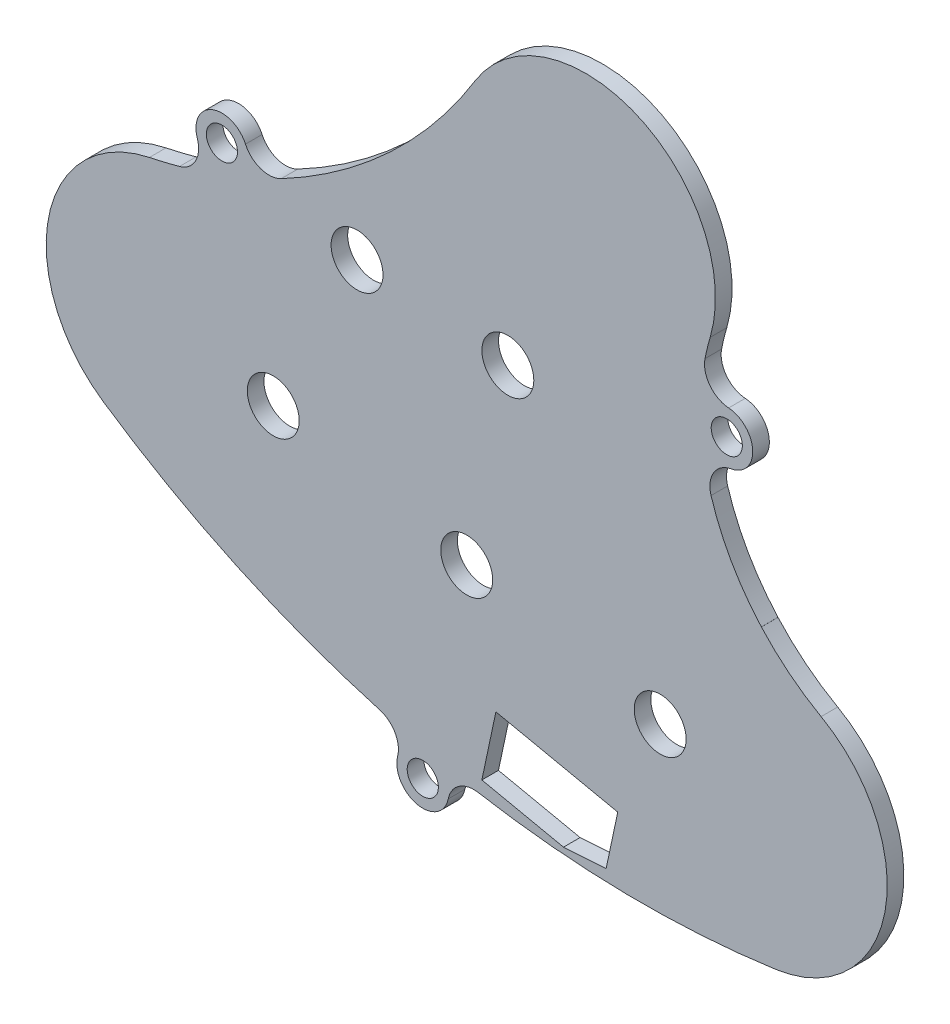
SolidWorks part; units mm, degrees
ref_plane "Front Plane" through (0, 0, 0) normal (0, 0, 1) x (1, 0, 0)
ref_plane "Top Plane" through (0, 0, 0) normal (0, 1, 0) x (1, 0, 0)
ref_plane "Right Plane" through (0, 0, 0) normal (1, 0, 0) x (0, 0, -1)
sketch "Sketch1" plane through (0, 0, 0) normal (0, 0, 1) x (1, 0, 0)
  line L0 (157.8919, 26.2701) -> (191.7747, 29.0915)
  line L1 (157.8919, 26.2701) -> (191.7747, 26.2701)
  line L2 (157.8919, 26.2701) -> (157.8919, 29.0915)
  line L3 (157.8919, 29.0915) -> (191.7747, 29.0915)
  line L4 (191.7747, 26.2701) -> (191.7747, 29.0915)
  line L5 (123.8919, 26.2701) -> (90.0092, 26.2701)
  line L6 (123.8919, 26.2701) -> (123.8919, 29.0915)
  line L7 (123.8919, 29.0915) -> (90.0092, 29.0915)
  line L8 (90.0092, 26.2701) -> (90.0092, 29.0915)
  line L9 (90.0092, 29.0915) -> (123.8919, 26.2701)
  line L10 (168.0919, 58.3601) -> (194.8735, 70.7292)
  line L11 (168.0919, 58.3601) -> (194.8735, 58.3601)
  line L12 (168.0919, 58.3601) -> (168.0919, 70.7292)
  line L13 (168.0919, 70.7292) -> (194.8735, 70.7292)
  line L14 (194.8735, 58.3601) -> (194.8735, 70.7292)
  line L15 (194.8735, 70.7292) -> (224.3587, 70.7292)
  line L16 (194.8735, 70.7292) -> (194.8735, 69.7923)
  line L17 (194.8735, 69.7923) -> (224.3587, 69.7923)
  line L18 (224.3587, 70.7292) -> (224.3587, 69.7923)
  line L19 (224.3587, 69.7923) -> (253.5106, 69.7923)
  line L20 (224.3587, 69.7923) -> (224.3587, 65.2742)
  line L21 (224.3587, 65.2742) -> (253.5106, 65.2742)
  line L22 (253.5106, 69.7923) -> (253.5106, 65.2742)
  line L23 (224.3587, 69.7923) -> (194.8735, 70.7292)
  line L24 (253.5106, 65.2742) -> (224.3587, 69.7923)
  line L25 (170.7502, 87.7401) -> (168.0919, 58.3601)
  line L26 (168.0919, 58.3601) -> (170.7502, 58.3601)
  line L27 (168.0919, 58.3601) -> (168.0919, 87.7401)
  line L28 (168.0919, 87.7401) -> (170.7502, 87.7401)
  line L29 (170.7502, 58.3601) -> (170.7502, 87.7401)
  line L30 (52.9966, 89.4705) -> (24.4119, 82.1791)
  line L31 (24.4119, 82.1791) -> (52.9966, 82.1791)
  line L32 (24.4119, 82.1791) -> (24.4119, 89.4705)
  line L33 (24.4119, 89.4705) -> (52.9966, 89.4705)
  line L34 (52.9966, 82.1791) -> (52.9966, 89.4705)
  line L35 (82.4966, 89.4705) -> (109.0019, 89.4705)
  line L36 (82.4966, 89.4705) -> (82.4966, 76.5201)
  line L37 (82.4966, 76.5201) -> (109.0019, 76.5201)
  line L38 (109.0019, 89.4705) -> (109.0019, 76.5201)
  line L39 (92.4554, 117.2387) -> (82.4966, 117.2387)
  line L40 (92.4554, 117.2387) -> (92.4554, 89.4705)
  line L41 (92.4554, 89.4705) -> (82.4966, 89.4705)
  line L42 (82.4966, 117.2387) -> (82.4966, 89.4705)
  line L43 (92.4554, 117.2387) -> (82.4966, 89.4705)
  line L44 (109.0019, 76.5201) -> (82.4966, 89.4705)
  circle A0 centre (123.8919, 26.2701) radius 14.25
  circle A1 centre (157.8919, 26.2701) radius 14.25
  circle A2 centre (90.0092, 29.0915) radius 14.25
  circle A3 centre (191.7747, 29.0915) radius 14.25
  circle A4 centre (82.4966, 89.4705) radius 11.25
  circle A5 centre (92.4554, 117.2387) radius 11.25
  circle A6 centre (52.9966, 89.4705) radius 11.25
  circle A7 centre (109.0019, 76.5201) radius 11.25
  circle A8 centre (24.4119, 82.1791) radius 11.25
  circle A9 centre (170.7502, 87.7401) radius 11.25
  circle A10 centre (168.0919, 58.3601) radius 11.25
  circle A11 centre (197.5318, 100.1092) radius 11.25
  circle A12 centre (194.8735, 70.7292) radius 11.25
  circle A13 centre (227.0169, 99.1723) radius 11.25
  circle A14 centre (224.3587, 69.7923) radius 11.25
  circle A15 centre (256.1689, 94.6541) radius 11.25
  circle A16 centre (253.5106, 65.2742) radius 11.25
  circle A17 centre (24.4119, 82.1791) radius 12
  circle A18 centre (52.9966, 89.4705) radius 12
  circle A19 centre (92.4554, 117.2387) radius 12
  circle A20 centre (82.4966, 89.4705) radius 12
  circle A21 centre (109.0019, 76.5201) radius 12
  circle A22 centre (168.0919, 58.3601) radius 12
  circle A23 centre (194.8735, 70.7292) radius 12
  circle A24 centre (224.3587, 69.7923) radius 12
  circle A25 centre (253.5106, 65.2742) radius 12
  circle A26 centre (256.1689, 94.6541) radius 12
  circle A27 centre (227.0169, 99.1723) radius 12
  circle A28 centre (197.5318, 100.1092) radius 12
  circle A29 centre (170.7502, 87.7401) radius 12
  circle A30 centre (191.7747, 29.0915) radius 15
  circle A31 centre (157.8919, 26.2701) radius 15
  circle A32 centre (123.8919, 26.2701) radius 15
  circle A33 centre (90.0092, 29.0915) radius 15
  circle A34 centre (173.429, 117.1182) radius 11.25
  circle A35 centre (173.429, 117.1182) radius 12
  dimension "D1" = 28.5
  dimension "D2" = 22.5
  dimension "D3" = 0.75
  dimension "D4" = 0.75
  dimension "D34" = 34
  dimension "D5" = 29.5
  dimension "D6" = 29.5
  dimension "D7" = 29.5
  dimension "D8" = 29.5
  dimension "D9" = 29.5
  dimension "D10" = 29.5
  dimension "D11" = 29.5
  dimension "D12" = 29.5
  dimension "D13" = 29.5
  dimension "D14" = 29.5
  dimension "D15" = 29.5
  dimension "D16" = 29.5
  dimension "D17" = 29.5
  dimension "D18" = 29.5
  dimension "D19" = 34
  dimension "D20" = 34
  dimension "D21" = 32.09
  dimension "D22" = 10.2
  dimension "D23" = 4.76
  dimension "D24" = 4.76
  dimension "D25" = 24.79
  dimension "D26" = 1.82
  dimension "D27" = 8.81
  dimension "D28" = 84.83
  dimension "D29" = 75.69
  dimension "D30" = 70.27
  dimension "D31" = 26.04
  dimension "D32" = 14.89
  dimension "D33" = 50.25
  dimension "D35" = 29.5
  dimension "D36" = 29.5
sketch "Sketch4" plane through (-30.2083, 20.075, 0) normal (0, 0, 1) x (0.9781, -0.2079, 0)
  line L0 (86.1706, 94.1917) -> (105.2206, 75.1417)
  line L1 (67.1206, 94.1917) -> (86.1706, 94.1917)
  line L2 (67.1206, 94.1917) -> (67.1206, 75.1417)
  line L3 (67.1206, 75.1417) -> (86.1706, 75.1417)
  line L4 (86.1706, 94.1917) -> (86.1706, 75.1417)
  line L5 (86.1706, 94.1917) -> (105.2206, 94.1917)
  line L6 (86.1706, 94.1917) -> (86.1706, 75.1417)
  line L7 (86.1706, 75.1417) -> (105.2206, 75.1417)
  line L8 (105.2206, 94.1917) -> (105.2206, 75.1417)
  line L9 (105.2206, 94.1917) -> (124.2706, 94.1917)
  line L10 (105.2206, 94.1917) -> (105.2206, 75.1417)
  line L11 (105.2206, 75.1417) -> (124.2706, 75.1417)
  line L12 (124.2706, 94.1917) -> (124.2706, 75.1417)
  line L13 (86.1706, 94.1917) -> (105.2206, 94.1917)
  line L14 (86.1706, 94.1917) -> (86.1706, 113.2417)
  line L15 (86.1706, 113.2417) -> (105.2206, 113.2417)
  line L16 (105.2206, 94.1917) -> (105.2206, 113.2417)
  line L17 (66.9585, 85.1784) -> (124.4326, 84.1551)
  point P14 (95.6956, 84.6667)
  point P15 (95.6956, 84.6667)
  dimension "D1" = 19.05
sketch "Sketch9" plane through (0, 0, 0) normal (0, 0, 1) x (1, 0, 0)
  line L1 (17.3619, 89.2291) -> (31.4619, 89.2291)
  line L2 (17.3619, 89.2291) -> (17.3619, 75.1291)
  line L3 (17.3619, 75.1291) -> (31.4619, 75.1291)
  line L4 (31.4619, 89.2291) -> (31.4619, 75.1291)
  line L5 (45.9466, 96.5205) -> (60.0466, 96.5205)
  line L6 (45.9466, 96.5205) -> (45.9466, 82.4205)
  line L7 (45.9466, 82.4205) -> (60.0466, 82.4205)
  line L8 (60.0466, 96.5205) -> (60.0466, 82.4205)
  line L9 (75.4466, 96.5205) -> (89.5466, 96.5205)
  line L10 (75.4466, 96.5205) -> (75.4466, 82.4205)
  line L11 (75.4466, 82.4205) -> (89.5466, 82.4205)
  line L12 (89.5466, 96.5205) -> (89.5466, 82.4205)
  line L13 (101.9519, 83.5701) -> (116.0519, 83.5701)
  line L14 (101.9519, 83.5701) -> (101.9519, 69.4701)
  line L15 (101.9519, 69.4701) -> (116.0519, 69.4701)
  line L16 (116.0519, 83.5701) -> (116.0519, 69.4701)
  line L17 (85.4054, 124.2887) -> (99.5054, 124.2887)
  line L18 (85.4054, 124.2887) -> (85.4054, 110.1887)
  line L19 (85.4054, 110.1887) -> (99.5054, 110.1887)
  line L20 (99.5054, 124.2887) -> (99.5054, 110.1887)
  line L21 (82.9592, 36.1415) -> (97.0592, 36.1415)
  line L22 (82.9592, 36.1415) -> (82.9592, 22.0415)
  line L23 (82.9592, 22.0415) -> (97.0592, 22.0415)
  line L24 (97.0592, 36.1415) -> (97.0592, 22.0415)
  line L25 (116.8419, 33.3201) -> (130.9419, 33.3201)
  line L26 (116.8419, 33.3201) -> (116.8419, 19.2201)
  line L27 (116.8419, 19.2201) -> (130.9419, 19.2201)
  line L28 (130.9419, 33.3201) -> (130.9419, 19.2201)
  line L29 (150.8419, 33.3201) -> (164.9419, 33.3201)
  line L30 (150.8419, 33.3201) -> (150.8419, 19.2201)
  line L31 (150.8419, 19.2201) -> (164.9419, 19.2201)
  line L32 (164.9419, 33.3201) -> (164.9419, 19.2201)
  line L33 (184.7247, 36.1415) -> (198.8247, 36.1415)
  line L34 (184.7247, 36.1415) -> (184.7247, 22.0415)
  line L35 (184.7247, 22.0415) -> (198.8247, 22.0415)
  line L36 (198.8247, 36.1415) -> (198.8247, 22.0415)
  line L37 (260.5606, 58.2242) -> (246.4606, 58.2242)
  line L38 (260.5606, 58.2242) -> (260.5606, 72.3242)
  line L39 (260.5606, 72.3242) -> (246.4606, 72.3242)
  line L40 (246.4606, 58.2242) -> (246.4606, 72.3242)
  line L41 (217.3087, 76.8423) -> (231.4087, 76.8423)
  line L42 (217.3087, 76.8423) -> (217.3087, 62.7423)
  line L43 (217.3087, 62.7423) -> (231.4087, 62.7423)
  line L44 (231.4087, 76.8423) -> (231.4087, 62.7423)
  line L45 (187.8235, 77.7792) -> (201.9235, 77.7792)
  line L46 (187.8235, 77.7792) -> (187.8235, 63.6792)
  line L47 (187.8235, 63.6792) -> (201.9235, 63.6792)
  line L48 (201.9235, 77.7792) -> (201.9235, 63.6792)
  line L49 (161.0419, 65.4101) -> (175.1419, 65.4101)
  line L50 (161.0419, 65.4101) -> (161.0419, 51.3101)
  line L51 (161.0419, 51.3101) -> (175.1419, 51.3101)
  line L52 (175.1419, 65.4101) -> (175.1419, 51.3101)
  line L53 (163.7002, 94.7901) -> (177.8002, 94.7901)
  line L54 (163.7002, 94.7901) -> (163.7002, 80.6901)
  line L55 (163.7002, 80.6901) -> (177.8002, 80.6901)
  line L56 (177.8002, 94.7901) -> (177.8002, 80.6901)
  line L57 (190.4818, 107.1592) -> (204.5818, 107.1592)
  line L58 (190.4818, 107.1592) -> (190.4818, 93.0592)
  line L59 (190.4818, 93.0592) -> (204.5818, 93.0592)
  line L60 (204.5818, 107.1592) -> (204.5818, 93.0592)
  line L61 (219.9669, 106.2223) -> (234.0669, 106.2223)
  line L62 (219.9669, 106.2223) -> (219.9669, 92.1223)
  line L63 (219.9669, 92.1223) -> (234.0669, 92.1223)
  line L64 (234.0669, 106.2223) -> (234.0669, 92.1223)
  line L65 (249.1189, 101.7041) -> (263.2189, 101.7041)
  line L66 (249.1189, 101.7041) -> (249.1189, 87.6041)
  line L67 (249.1189, 87.6041) -> (263.2189, 87.6041)
  line L68 (263.2189, 101.7041) -> (263.2189, 87.6041)
  line L69 (166.379, 124.1682) -> (180.479, 124.1682)
  line L70 (166.379, 124.1682) -> (166.379, 110.0682)
  line L71 (166.379, 110.0682) -> (180.479, 110.0682)
  line L72 (180.479, 124.1682) -> (180.479, 110.0682)
  point P72 (24.4119, 89.2291)
  point P74 (52.9966, 96.5205)
  point P76 (82.4966, 96.5205)
  point P78 (92.4554, 124.2887)
  point P80 (109.0019, 83.5701)
  point P82 (90.0092, 36.1415)
  point P84 (123.8919, 33.3201)
  point P86 (157.8919, 33.3201)
  point P88 (191.7747, 36.1415)
  point P90 (168.0919, 65.4101)
  point P92 (170.7502, 94.7901)
  point P94 (173.429, 124.1682)
  point P96 (197.5318, 107.1592)
  point P98 (227.0169, 106.2223)
  point P100 (256.1689, 101.7041)
  point P102 (194.8735, 77.7792)
  point P104 (224.3587, 76.8423)
  point P106 (253.5106, 72.3242)
  point P108 (17.3619, 82.1791)
  point P109 (45.9466, 89.4705)
  point P110 (75.4466, 89.4705)
  point P111 (101.9519, 76.5201)
  point P112 (85.4054, 117.2387)
  point P113 (82.9592, 29.0915)
  point P114 (116.8419, 26.2701)
  point P115 (150.8419, 26.2701)
  point P116 (184.7247, 29.0915)
  point P118 (161.0419, 58.3601)
  point P119 (187.8235, 70.7292)
  point P120 (217.3087, 69.7923)
  point P121 (246.4606, 65.2742)
  point P122 (163.7002, 87.7401)
  point P123 (190.4818, 100.1092)
  point P124 (219.9669, 99.1723)
  point P125 (249.1189, 94.6541)
  point P126 (166.379, 117.1182)
  dimension "D1" = 14.1
sketch "Sketch10" plane through (-22.0981, 19.3454, 0) normal (0, 0, 1) x (0.9781, -0.2079, 0)
  line L1 (61.5108, 90.7441) -> (75.6108, 90.7441)
  line L2 (61.5108, 90.7441) -> (61.5108, 76.6441)
  line L3 (61.5108, 76.6441) -> (75.6108, 76.6441)
  line L4 (75.6108, 90.7441) -> (75.6108, 76.6441)
  line L5 (80.5608, 90.7441) -> (94.6608, 90.7441)
  line L6 (80.5608, 90.7441) -> (80.5608, 76.6441)
  line L7 (80.5608, 76.6441) -> (94.6608, 76.6441)
  line L8 (94.6608, 90.7441) -> (94.6608, 76.6441)
  line L9 (99.6108, 90.7441) -> (113.7108, 90.7441)
  line L10 (99.6108, 90.7441) -> (99.6108, 76.6441)
  line L11 (99.6108, 76.6441) -> (113.7108, 76.6441)
  line L12 (113.7108, 90.7441) -> (113.7108, 76.6441)
  line L13 (80.5608, 109.7941) -> (94.6608, 109.7941)
  line L14 (80.5608, 109.7941) -> (80.5608, 95.6941)
  line L15 (80.5608, 95.6941) -> (94.6608, 95.6941)
  line L16 (94.6608, 109.7941) -> (94.6608, 95.6941)
  line L17 (50.5121, 89.6359) -> (53.4436, 75.8441) construction
  line L18 (59.0358, 93.2191) -> (78.0858, 93.2191) construction
  line L19 (78.0858, 112.2691) -> (97.1358, 112.2691) construction
  line L20 (97.1358, 93.2191) -> (116.1858, 93.2191) construction
  line L21 (78.0858, 93.2191) -> (78.0858, 112.2691) construction
  line L23 (59.0358, 93.2191) -> (59.0358, 74.1691) construction
  point P16 (75.6108, 83.6941)
  point P17 (94.6608, 83.6941)
  point P18 (113.7108, 83.6941)
  point P19 (87.6108, 90.7441)
  point P20 (87.6108, 109.7941)
  point P23 (68.5608, 90.7441)
  point P26 (68.5608, 93.2191)
  point P29 (87.6108, 112.2691)
  point P30 (106.6608, 90.7441)
  point P33 (106.6608, 93.2191)
  point P34 (80.5608, 102.7441)
  point P37 (78.0858, 102.7441)
  point P42 (59.0358, 83.6941)
  point P43 (61.5108, 83.6941)
sketch "Sketch14" plane through (0, 0, 0) normal (0, 0, 1) x (1, 0, 0)
  line L0 (165.1144, 80.6901) -> (163.7002, 82.1043)
  line L1 (163.7002, 93.3758) -> (165.1144, 94.7901)
  line L2 (177.8002, 93.3758) -> (176.386, 94.7901)
  line L3 (179.0648, 110.0682) -> (180.479, 111.4824)
  line L4 (166.379, 111.4824) -> (167.7932, 110.0682)
  line L5 (166.379, 122.754) -> (167.7932, 124.1682)
  line L6 (179.0648, 124.1682) -> (180.479, 122.754)
  line L7 (203.1676, 93.0592) -> (204.5818, 94.4734)
  line L8 (17.3619, 89.2291) -> (17.3619, 75.1291) construction
  line L9 (17.3619, 89.2291) -> (31.4619, 89.2291) construction
  line L10 (17.3619, 87.8149) -> (18.7761, 89.2291)
  line L11 (17.3619, 75.1291) -> (31.4619, 75.1291) construction
  line L12 (31.4619, 89.2291) -> (31.4619, 75.1291) construction
  line L13 (45.9466, 96.5205) -> (60.0466, 96.5205) construction
  line L14 (60.0466, 96.5205) -> (60.0466, 82.4205) construction
  line L15 (45.9466, 96.5205) -> (45.9466, 82.4205) construction
  line L16 (45.9466, 82.4205) -> (60.0466, 82.4205) construction
  line L17 (85.4054, 124.2887) -> (85.4054, 110.1887) construction
  line L18 (85.4054, 124.2887) -> (99.5054, 124.2887) construction
  line L19 (99.5054, 124.2887) -> (99.5054, 110.1887) construction
  line L20 (85.4054, 110.1887) -> (99.5054, 110.1887) construction
  line L21 (101.9519, 83.5701) -> (101.9519, 69.4701) construction
  line L22 (101.9519, 83.5701) -> (116.0519, 83.5701) construction
  line L23 (116.0519, 83.5701) -> (116.0519, 69.4701) construction
  line L24 (101.9519, 69.4701) -> (116.0519, 69.4701) construction
  line L25 (91.2712, 73.6044) -> (105.0631, 70.6729) construction
  line L26 (107.9947, 84.4647) -> (105.0631, 70.6729) construction
  line L27 (94.2028, 87.3963) -> (107.9947, 84.4647) construction
  line L28 (94.2028, 87.3963) -> (91.2712, 73.6044) construction
  line L29 (72.6375, 77.5651) -> (86.4294, 74.6336) construction
  line L30 (89.361, 88.4255) -> (86.4294, 74.6336) construction
  line L31 (75.5691, 91.357) -> (89.361, 88.4255) construction
  line L32 (75.5691, 91.357) -> (72.6375, 77.5651) construction
  line L33 (56.9354, 95.3177) -> (54.0038, 81.5259) construction
  line L34 (56.9354, 95.3177) -> (70.7273, 92.3862) construction
  line L35 (70.7273, 92.3862) -> (67.7957, 78.5943) construction
  line L36 (54.0038, 81.5259) -> (67.7957, 78.5943) construction
  line L37 (76.5983, 96.1988) -> (90.3901, 93.2673) construction
  line L38 (93.3217, 107.0592) -> (90.3901, 93.2673) construction
  line L39 (79.5298, 109.9907) -> (76.5983, 96.1988) construction
  line L40 (79.5298, 109.9907) -> (93.3217, 107.0592) construction
  line L41 (82.9592, 36.1415) -> (82.9592, 22.0415) construction
  line L42 (82.9592, 36.1415) -> (97.0592, 36.1415) construction
  line L43 (82.9592, 22.0415) -> (97.0592, 22.0415) construction
  line L44 (97.0592, 36.1415) -> (97.0592, 22.0415) construction
  line L45 (116.8419, 33.3201) -> (116.8419, 19.2201) construction
  line L46 (116.8419, 33.3201) -> (130.9419, 33.3201) construction
  line L47 (116.8419, 19.2201) -> (130.9419, 19.2201) construction
  line L48 (130.9419, 33.3201) -> (130.9419, 19.2201) construction
  line L49 (150.8419, 33.3201) -> (150.8419, 19.2201) construction
  line L50 (150.8419, 33.3201) -> (164.9419, 33.3201) construction
  line L51 (164.9419, 33.3201) -> (164.9419, 19.2201) construction
  line L52 (150.8419, 19.2201) -> (164.9419, 19.2201) construction
  line L53 (184.7247, 36.1415) -> (184.7247, 22.0415) construction
  line L54 (184.7247, 22.0415) -> (198.8247, 22.0415) construction
  line L55 (198.8247, 36.1415) -> (198.8247, 22.0415) construction
  line L56 (184.7247, 36.1415) -> (198.8247, 36.1415) construction
  line L57 (161.0419, 65.4101) -> (175.1419, 65.4101) construction
  line L58 (175.1419, 65.4101) -> (175.1419, 51.3101) construction
  line L59 (161.0419, 51.3101) -> (175.1419, 51.3101) construction
  line L60 (161.0419, 65.4101) -> (161.0419, 51.3101) construction
  line L61 (187.8235, 77.7792) -> (187.8235, 63.6792) construction
  line L62 (187.8235, 77.7792) -> (201.9235, 77.7792) construction
  line L63 (187.8235, 63.6792) -> (201.9235, 63.6792) construction
  line L64 (201.9235, 77.7792) -> (201.9235, 63.6792) construction
  line L65 (217.3087, 76.8423) -> (217.3087, 62.7423) construction
  line L66 (217.3087, 76.8423) -> (231.4087, 76.8423) construction
  line L67 (231.4087, 76.8423) -> (231.4087, 62.7423) construction
  line L68 (217.3087, 62.7423) -> (231.4087, 62.7423) construction
  line L69 (260.5606, 58.2242) -> (246.4606, 58.2242) construction
  line L70 (260.5606, 58.2242) -> (260.5606, 72.3242) construction
  line L71 (246.4606, 58.2242) -> (246.4606, 72.3242) construction
  line L72 (260.5606, 72.3242) -> (246.4606, 72.3242) construction
  line L73 (249.1189, 101.7041) -> (263.2189, 101.7041) construction
  line L74 (263.2189, 101.7041) -> (263.2189, 87.6041) construction
  line L75 (249.1189, 87.6041) -> (263.2189, 87.6041) construction
  line L76 (249.1189, 101.7041) -> (249.1189, 87.6041) construction
  line L77 (219.9669, 106.2223) -> (219.9669, 92.1223) construction
  line L78 (219.9669, 106.2223) -> (234.0669, 106.2223) construction
  line L79 (234.0669, 106.2223) -> (234.0669, 92.1223) construction
  line L80 (219.9669, 92.1223) -> (234.0669, 92.1223) construction
  line L81 (190.4818, 107.1592) -> (204.5818, 107.1592) construction
  line L82 (204.5818, 107.1592) -> (204.5818, 93.0592) construction
  line L83 (190.4818, 93.0592) -> (204.5818, 93.0592) construction
  line L84 (190.4818, 107.1592) -> (190.4818, 93.0592) construction
  line L85 (163.7002, 94.7901) -> (177.8002, 94.7901) construction
  line L86 (177.8002, 94.7901) -> (177.8002, 80.6901) construction
  line L87 (163.7002, 80.6901) -> (177.8002, 80.6901) construction
  line L88 (163.7002, 94.7901) -> (163.7002, 80.6901) construction
  line L89 (180.479, 124.1682) -> (180.479, 110.0682) construction
  line L90 (166.379, 110.0682) -> (180.479, 110.0682) construction
  line L91 (166.379, 124.1682) -> (166.379, 110.0682) construction
  line L92 (166.379, 124.1682) -> (180.479, 124.1682) construction
  line L93 (17.3619, 76.5433) -> (18.7761, 75.1291)
  line L94 (30.0477, 75.1291) -> (31.4619, 76.5433)
  line L95 (31.4619, 87.8149) -> (30.0477, 89.2291)
  line L96 (45.9466, 95.1063) -> (47.3608, 96.5205)
  line L97 (45.9466, 83.8347) -> (47.3608, 82.4205)
  line L98 (54.2979, 82.9092) -> (55.3871, 81.2318)
  line L99 (58.6323, 82.4205) -> (60.0466, 83.8347)
  line L100 (56.6413, 93.9344) -> (58.3187, 95.0237)
  line L101 (58.6323, 96.5205) -> (60.0466, 95.1063)
  line L102 (69.3439, 92.6802) -> (70.4332, 91.0029)
  line L103 (68.0897, 79.9776) -> (66.4124, 78.8883)
  line L104 (75.2751, 89.9737) -> (76.9524, 91.063)
  line L105 (72.9316, 78.9484) -> (74.0208, 77.2711)
  line L106 (85.0461, 74.9276) -> (86.7234, 76.0169)
  line L107 (89.0669, 87.0421) -> (87.9777, 88.7195)
  line L108 (89.0068, 93.5613) -> (90.6842, 94.6506)
  line L109 (76.8923, 97.5822) -> (77.9816, 95.9048)
  line L110 (91.9384, 107.3532) -> (93.0277, 105.6759)
  line L111 (79.2358, 108.6074) -> (80.9131, 109.6967)
  line L112 (85.4054, 111.6029) -> (86.8196, 110.1887)
  line L113 (98.0912, 110.1887) -> (99.5054, 111.6029)
  line L114 (98.0912, 124.2887) -> (99.5054, 122.8745)
  line L115 (85.4054, 122.8745) -> (86.8196, 124.2887)
  line L116 (93.9088, 86.013) -> (95.5861, 87.1023)
  line L117 (91.5653, 74.9877) -> (92.6546, 73.3104)
  line L118 (103.6798, 70.9669) -> (105.3572, 72.0562)
  line L119 (106.6114, 84.7588) -> (107.7006, 83.0814)
  line L120 (101.9519, 82.1559) -> (103.3662, 83.5701)
  line L121 (101.9519, 70.8843) -> (103.3662, 69.4701)
  line L122 (114.6377, 69.4701) -> (116.0519, 70.8843)
  line L123 (116.0519, 82.1559) -> (114.6377, 83.5701)
  line L124 (82.9592, 34.7272) -> (84.3734, 36.1415)
  line L125 (82.9592, 23.4557) -> (84.3734, 22.0415)
  line L126 (95.645, 22.0415) -> (97.0592, 23.4557)
  line L127 (97.0592, 34.7272) -> (95.645, 36.1415)
  line L128 (116.8419, 31.9059) -> (118.2562, 33.3201)
  line L129 (116.8419, 20.6343) -> (118.2562, 19.2201)
  line L130 (129.5277, 19.2201) -> (130.9419, 20.6343)
  line L131 (130.9419, 31.9059) -> (129.5277, 33.3201)
  line L132 (150.8419, 31.9059) -> (152.2562, 33.3201)
  line L133 (150.8419, 20.6343) -> (152.2562, 19.2201)
  line L134 (163.5277, 19.2201) -> (164.9419, 20.6343)
  line L135 (164.9419, 31.9059) -> (163.5277, 33.3201)
  line L136 (184.7247, 34.7272) -> (186.1389, 36.1415)
  line L137 (184.7247, 23.4557) -> (186.1389, 22.0415)
  line L138 (197.4105, 22.0415) -> (198.8247, 23.4557)
  line L139 (198.8247, 34.7272) -> (197.4105, 36.1415)
  line L140 (173.7277, 51.3101) -> (175.1419, 52.7243)
  line L141 (161.0419, 52.7243) -> (162.4562, 51.3101)
  line L142 (161.0419, 63.9959) -> (162.4562, 65.4101)
  line L143 (173.7277, 65.4101) -> (175.1419, 63.9959)
  line L144 (187.8235, 65.0934) -> (189.2378, 63.6792)
  line L145 (200.5093, 63.6792) -> (201.9235, 65.0934)
  line L146 (200.5093, 77.7792) -> (201.9235, 76.365)
  line L147 (187.8235, 76.365) -> (189.2378, 77.7792)
  line L148 (176.386, 80.6901) -> (177.8002, 82.1043)
  line L149 (204.5818, 105.745) -> (203.1676, 107.1592)
  line L150 (191.896, 107.1592) -> (190.4818, 105.745)
  line L151 (190.4818, 94.4734) -> (191.896, 93.0592)
  line L152 (219.9669, 104.8081) -> (221.3812, 106.2223)
  line L153 (232.6527, 106.2223) -> (234.0669, 104.8081)
  line L154 (234.0669, 93.5365) -> (232.6527, 92.1223)
  line L155 (219.9669, 93.5365) -> (221.3812, 92.1223)
  line L156 (229.9944, 76.8423) -> (231.4087, 75.4281)
  line L157 (217.3087, 75.4281) -> (218.7229, 76.8423)
  line L158 (217.3087, 64.1565) -> (218.7229, 62.7423)
  line L159 (229.9944, 62.7423) -> (231.4087, 64.1565)
  line L160 (259.1464, 72.3242) -> (260.5606, 70.9099)
  line L161 (246.4606, 70.9099) -> (247.8748, 72.3242)
  line L162 (259.1464, 58.2242) -> (260.5606, 59.6384)
  line L163 (247.8748, 58.2242) -> (246.4606, 59.6384)
  line L164 (261.8047, 87.6041) -> (263.2189, 89.0183)
  line L165 (249.1189, 89.0183) -> (250.5331, 87.6041)
  line L166 (249.1189, 100.2899) -> (250.5331, 101.7041)
  line L167 (261.8047, 101.7041) -> (263.2189, 100.2899)
  line L168 (75.4466, 96.5205) -> (75.4466, 82.4205) construction
  line L169 (75.4466, 96.5205) -> (89.5466, 96.5205) construction
  line L170 (89.5466, 96.5205) -> (89.5466, 82.4205) construction
  line L171 (75.4466, 82.4205) -> (89.5466, 82.4205) construction
  line L172 (76.8608, 96.5205) -> (75.4466, 95.1063)
  line L173 (88.1323, 96.5205) -> (89.5466, 95.1063)
  line L174 (89.5466, 83.8347) -> (88.1323, 82.4205)
  line L175 (75.4466, 83.8347) -> (76.8608, 82.4205)
  arc A0 (17.3619, 87.8149) -> (18.7761, 89.2291) centre (18.069, 88.522) cw
  arc A1 (18.7761, 75.1291) -> (17.3619, 76.5433) centre (18.069, 75.8362) cw
  arc A2 (31.4619, 76.5433) -> (30.0477, 75.1291) centre (30.7548, 75.8362) cw
  arc A3 (30.0477, 89.2291) -> (31.4619, 87.8149) centre (30.7548, 88.522) cw
  arc A4 (58.6323, 96.5205) -> (60.0466, 95.1063) centre (59.3394, 95.8134) cw
  arc A5 (45.9466, 95.1063) -> (47.3608, 96.5205) centre (46.6537, 95.8134) cw
  arc A6 (47.3608, 82.4205) -> (45.9466, 83.8347) centre (46.6537, 83.1276) cw
  arc A7 (60.0466, 83.8347) -> (58.6323, 82.4205) centre (59.3394, 83.1276) cw
  arc A8 (85.4054, 122.8745) -> (86.8196, 124.2887) centre (86.1125, 123.5816) cw
  arc A9 (98.0912, 124.2887) -> (99.5054, 122.8745) centre (98.7983, 123.5816) cw
  arc A10 (99.5054, 111.6029) -> (98.0912, 110.1887) centre (98.7983, 110.8958) cw
  arc A11 (85.4054, 111.6029) -> (86.8196, 110.1887) centre (86.1125, 110.8958) ccw
  arc A12 (101.9519, 82.1559) -> (103.3662, 83.5701) centre (102.6591, 82.863) cw
  arc A13 (114.6377, 83.5701) -> (116.0519, 82.1559) centre (115.3448, 82.863) cw
  arc A14 (116.0519, 70.8843) -> (114.6377, 69.4701) centre (115.3448, 70.1772) cw
  arc A15 (101.9519, 70.8843) -> (103.3662, 69.4701) centre (102.6591, 70.1772) ccw
  arc A16 (103.6798, 70.9669) -> (105.3572, 72.0562) centre (104.5185, 71.5115) ccw
  arc A17 (106.6114, 84.7588) -> (107.7006, 83.0814) centre (107.156, 83.9201) cw
  arc A18 (93.9088, 86.013) -> (95.5861, 87.1023) centre (94.7474, 86.5576) cw
  arc A19 (91.5653, 74.9877) -> (92.6546, 73.3104) centre (92.1099, 74.1491) ccw
  arc A20 (85.0461, 74.9276) -> (86.7234, 76.0169) centre (85.8848, 75.4722) ccw
  arc A21 (87.9777, 88.7195) -> (89.0669, 87.0421) centre (88.5223, 87.8808) cw
  arc A22 (75.2751, 89.9737) -> (76.9524, 91.063) centre (76.1137, 90.5183) cw
  arc A23 (72.9316, 78.9484) -> (74.0208, 77.2711) centre (73.4762, 78.1098) ccw
  arc A24 (56.6413, 93.9344) -> (58.3187, 95.0237) centre (57.48, 94.4791) cw
  arc A25 (69.3439, 92.6802) -> (70.4332, 91.0029) centre (69.8886, 91.8415) cw
  arc A26 (68.0897, 79.9776) -> (66.4124, 78.8883) centre (67.2511, 79.433) cw
  arc A27 (54.2979, 82.9092) -> (55.3871, 81.2318) centre (54.8425, 82.0705) ccw
  arc A28 (89.0068, 93.5613) -> (90.6842, 94.6506) centre (89.8455, 94.106) ccw
  arc A29 (76.8923, 97.5822) -> (77.9816, 95.9048) centre (77.4369, 96.7435) ccw
  arc A30 (79.2358, 108.6074) -> (80.9131, 109.6967) centre (80.0744, 109.1521) cw
  arc A31 (91.9384, 107.3532) -> (93.0277, 105.6759) centre (92.483, 106.5145) cw
  arc A32 (82.9592, 34.7272) -> (84.3734, 36.1415) centre (83.6663, 35.4344) cw
  arc A33 (82.9592, 23.4557) -> (84.3734, 22.0415) centre (83.6663, 22.7486) ccw
  arc A34 (95.645, 22.0415) -> (97.0592, 23.4557) centre (96.3521, 22.7486) ccw
  arc A35 (95.645, 36.1415) -> (97.0592, 34.7272) centre (96.3521, 35.4344) cw
  arc A36 (116.8419, 31.9059) -> (118.2562, 33.3201) centre (117.5491, 32.613) cw
  arc A37 (116.8419, 20.6343) -> (118.2562, 19.2201) centre (117.5491, 19.9272) ccw
  arc A38 (129.5277, 19.2201) -> (130.9419, 20.6343) centre (130.2348, 19.9272) ccw
  arc A39 (129.5277, 33.3201) -> (130.9419, 31.9059) centre (130.2348, 32.613) cw
  arc A40 (150.8419, 31.9059) -> (152.2562, 33.3201) centre (151.5491, 32.613) cw
  arc A41 (163.5277, 33.3201) -> (164.9419, 31.9059) centre (164.2348, 32.613) cw
  arc A42 (164.9419, 20.6343) -> (163.5277, 19.2201) centre (164.2348, 19.9272) cw
  arc A43 (150.8419, 20.6343) -> (152.2562, 19.2201) centre (151.5491, 19.9272) ccw
  arc A44 (184.7247, 23.4557) -> (186.1389, 22.0415) centre (185.4318, 22.7486) ccw
  arc A45 (197.4105, 22.0415) -> (198.8247, 23.4557) centre (198.1176, 22.7486) ccw
  arc A46 (197.4105, 36.1415) -> (198.8247, 34.7272) centre (198.1176, 35.4344) cw
  arc A47 (184.7247, 34.7272) -> (186.1389, 36.1415) centre (185.4318, 35.4344) cw
  arc A48 (173.7277, 65.4101) -> (175.1419, 63.9959) centre (174.4348, 64.703) cw
  arc A49 (175.1419, 52.7243) -> (173.7277, 51.3101) centre (174.4348, 52.0172) cw
  arc A50 (161.0419, 52.7243) -> (162.4562, 51.3101) centre (161.7491, 52.0172) ccw
  arc A51 (161.0419, 63.9959) -> (162.4562, 65.4101) centre (161.7491, 64.703) cw
  arc A52 (187.8235, 76.365) -> (189.2378, 77.7792) centre (188.5306, 77.0721) cw
  arc A53 (187.8235, 65.0934) -> (189.2378, 63.6792) centre (188.5306, 64.3863) ccw
  arc A54 (200.5093, 63.6792) -> (201.9235, 65.0934) centre (201.2164, 64.3863) ccw
  arc A55 (200.5093, 77.7792) -> (201.9235, 76.365) centre (201.2164, 77.0721) cw
  arc A56 (217.3087, 75.4281) -> (218.7229, 76.8423) centre (218.0158, 76.1352) cw
  arc A57 (229.9944, 76.8423) -> (231.4087, 75.4281) centre (230.7016, 76.1352) cw
  arc A58 (231.4087, 64.1565) -> (229.9944, 62.7423) centre (230.7016, 63.4494) cw
  arc A59 (217.3087, 64.1565) -> (218.7229, 62.7423) centre (218.0158, 63.4494) ccw
  arc A60 (259.1464, 58.2242) -> (260.5606, 59.6384) centre (259.8535, 58.9313) ccw
  arc A61 (246.4606, 59.6384) -> (247.8748, 58.2242) centre (247.1677, 58.9313) ccw
  arc A62 (246.4606, 70.9099) -> (247.8748, 72.3242) centre (247.1677, 71.617) cw
  arc A63 (259.1464, 72.3242) -> (260.5606, 70.9099) centre (259.8535, 71.617) cw
  arc A64 (261.8047, 101.7041) -> (263.2189, 100.2899) centre (262.5118, 100.997) cw
  arc A65 (263.2189, 89.0183) -> (261.8047, 87.6041) centre (262.5118, 88.3112) cw
  arc A66 (250.5331, 87.6041) -> (249.1189, 89.0183) centre (249.826, 88.3112) cw
  arc A67 (249.1189, 100.2899) -> (250.5331, 101.7041) centre (249.826, 100.997) cw
  arc A68 (219.9669, 104.8081) -> (221.3812, 106.2223) centre (220.674, 105.5152) cw
  arc A69 (232.6527, 106.2223) -> (234.0669, 104.8081) centre (233.3598, 105.5152) cw
  arc A70 (234.0669, 93.5365) -> (232.6527, 92.1223) centre (233.3598, 92.8294) cw
  arc A71 (221.3812, 92.1223) -> (219.9669, 93.5365) centre (220.674, 92.8294) cw
  arc A72 (203.1676, 107.1592) -> (204.5818, 105.745) centre (203.8747, 106.4521) cw
  arc A73 (204.5818, 94.4734) -> (203.1676, 93.0592) centre (203.8747, 93.7663) cw
  arc A74 (191.896, 93.0592) -> (190.4818, 94.4734) centre (191.1889, 93.7663) cw
  arc A75 (190.4818, 105.745) -> (191.896, 107.1592) centre (191.1889, 106.4521) cw
  arc A76 (176.386, 94.7901) -> (177.8002, 93.3758) centre (177.0931, 94.0829) cw
  arc A77 (177.8002, 82.1043) -> (176.386, 80.6901) centre (177.0931, 81.3972) cw
  arc A78 (165.1144, 80.6901) -> (163.7002, 82.1043) centre (164.4073, 81.3972) cw
  arc A79 (163.7002, 93.3758) -> (165.1144, 94.7901) centre (164.4073, 94.0829) cw
  arc A80 (180.479, 111.4824) -> (179.0648, 110.0682) centre (179.7719, 110.7753) cw
  arc A81 (167.7932, 110.0682) -> (166.379, 111.4824) centre (167.0861, 110.7753) cw
  arc A82 (179.0648, 124.1682) -> (180.479, 122.754) centre (179.7719, 123.4611) cw
  arc A83 (166.379, 122.754) -> (167.7932, 124.1682) centre (167.0861, 123.4611) cw
  arc A84 (75.4466, 95.1063) -> (76.8608, 96.5205) centre (76.1537, 95.8134) cw
  arc A85 (88.1323, 96.5205) -> (89.5466, 95.1063) centre (88.8394, 95.8134) cw
  arc A86 (89.5466, 83.8347) -> (88.1323, 82.4205) centre (88.8394, 83.1276) cw
  arc A87 (76.8608, 82.4205) -> (75.4466, 83.8347) centre (76.1537, 83.1276) cw
  dimension "D1" = 45
  dimension "D2" = 1
  dimension "D71" = 45
  dimension "D3" = 45
  dimension "D4" = 45
  dimension "D5" = 45
  dimension "D6" = 45
  dimension "D7" = 45
  dimension "D8" = 45
  dimension "D9" = 45
  dimension "D10" = 45
  dimension "D11" = 45
  dimension "D12" = 45
  dimension "D13" = 45
  dimension "D14" = 45
  dimension "D15" = 45
  dimension "D16" = 45
  dimension "D17" = 45
  dimension "D18" = 45
  dimension "D19" = 45
  dimension "D20" = 45
  dimension "D21" = 45
  dimension "D22" = 45
  dimension "D23" = 45
  dimension "D24" = 45
  dimension "D25" = 45
  dimension "D26" = 45
  dimension "D27" = 45
  dimension "D28" = 45
  dimension "D29" = 45
  dimension "D30" = 45
  dimension "D31" = 45
  dimension "D32" = 45
  dimension "D33" = 45
  dimension "D34" = 45
  dimension "D35" = 45
  dimension "D36" = 45
  dimension "D37" = 45
  dimension "D38" = 45
  dimension "D39" = 45
  dimension "D40" = 45
  dimension "D41" = 45
  dimension "D42" = 45
  dimension "D43" = 45
  dimension "D44" = 45
  dimension "D45" = 45
  dimension "D46" = 45
  dimension "D47" = 45
  dimension "D48" = 45
  dimension "D49" = 45
  dimension "D50" = 45
  dimension "D51" = 45
  dimension "D52" = 45
  dimension "D53" = 45
  dimension "D54" = 45
  dimension "D55" = 45
  dimension "D56" = 45
  dimension "D57" = 45
  dimension "D58" = 45
  dimension "D59" = 45
  dimension "D60" = 45
  dimension "D61" = 45
  dimension "D62" = 45
  dimension "D63" = 45
  dimension "D64" = 45
  dimension "D65" = 45
  dimension "D66" = 45
  dimension "D67" = 45
  dimension "D68" = 45
  dimension "D69" = 45
  dimension "D70" = 45
  dimension "D72" = 45
  dimension "D73" = 45
  dimension "D74" = 45
  dimension "D75" = 45
  dimension "D76" = 45
  dimension "D77" = 45
  dimension "D78" = 45
  dimension "D79" = 45
  dimension "D80" = 45
  dimension "D81" = 45
  dimension "D82" = 45
  dimension "D83" = 45
  dimension "D84" = 45
  dimension "D85" = 45
  dimension "D86" = 45
  dimension "D87" = 45
  dimension "D88" = 45
  dimension "D89" = 45
sketch "Sketch16" plane through (0, 0, 0) normal (0, 0, 1) x (1, 0, 0)
  line L0 (81.5092, 30.6915) -> (98.5092, 30.6915)
  line L5 (17.3619, 89.2291) -> (17.3619, 75.1291) construction
  line L6 (81.5092, 30.6915) -> (81.5092, 27.4915)
  line L7 (17.3619, 75.1291) -> (31.4619, 75.1291) construction
  line L8 (15.9119, 83.7791) -> (32.9119, 83.7791)
  line L9 (15.9119, 83.7791) -> (15.9119, 80.5791)
  line L10 (15.9119, 80.5791) -> (32.9119, 80.5791)
  line L11 (32.9119, 83.7791) -> (32.9119, 80.5791)
  line L12 (81.5092, 27.4915) -> (98.5092, 27.4915)
  line L13 (98.5092, 30.6915) -> (98.5092, 27.4915)
  line L14 (115.3919, 27.8701) -> (132.3919, 27.8701)
  line L15 (115.3919, 27.8701) -> (115.3919, 24.6701)
  line L16 (115.3919, 24.6701) -> (132.3919, 24.6701)
  line L17 (132.3919, 27.8701) -> (132.3919, 24.6701)
  line L18 (149.3919, 27.8701) -> (166.3919, 27.8701)
  line L19 (149.3919, 27.8701) -> (149.3919, 24.6701)
  line L20 (149.3919, 24.6701) -> (166.3919, 24.6701)
  line L21 (166.3919, 27.8701) -> (166.3919, 24.6701)
  line L22 (183.2747, 30.6915) -> (200.2747, 30.6915)
  line L23 (183.2747, 30.6915) -> (183.2747, 27.4915)
  line L24 (183.2747, 27.4915) -> (200.2747, 27.4915)
  line L25 (200.2747, 30.6915) -> (200.2747, 27.4915)
  line L26 (44.4966, 91.5705) -> (61.4966, 91.5705)
  line L27 (44.4966, 91.5705) -> (44.4966, 88.3705)
  line L28 (44.4966, 88.3705) -> (61.4966, 88.3705)
  line L29 (61.4966, 91.5705) -> (61.4966, 88.3705)
  line L30 (73.9966, 91.5705) -> (90.9966, 91.5705)
  line L31 (73.9966, 91.5705) -> (73.9966, 88.3705)
  line L32 (73.9966, 88.3705) -> (90.9966, 88.3705)
  line L33 (90.9966, 91.5705) -> (90.9966, 88.3705)
  line L34 (100.5019, 78.6201) -> (117.5019, 78.6201)
  line L35 (100.5019, 78.6201) -> (100.5019, 75.4201)
  line L36 (100.5019, 75.4201) -> (117.5019, 75.4201)
  line L37 (117.5019, 78.6201) -> (117.5019, 75.4201)
  line L38 (83.9554, 119.3387) -> (100.9554, 119.3387)
  line L39 (83.9554, 119.3387) -> (83.9554, 116.1387)
  line L40 (83.9554, 116.1387) -> (100.9554, 116.1387)
  line L41 (100.9554, 119.3387) -> (100.9554, 116.1387)
  line L42 (164.929, 118.7182) -> (181.929, 118.7182)
  line L43 (164.929, 118.7182) -> (164.929, 115.5182)
  line L44 (164.929, 115.5182) -> (181.929, 115.5182)
  line L45 (181.929, 118.7182) -> (181.929, 115.5182)
  line L46 (162.2502, 89.3401) -> (179.2502, 89.3401)
  line L47 (162.2502, 89.3401) -> (162.2502, 86.1401)
  line L48 (162.2502, 86.1401) -> (179.2502, 86.1401)
  line L49 (179.2502, 89.3401) -> (179.2502, 86.1401)
  line L50 (189.0318, 101.7092) -> (206.0318, 101.7092)
  line L51 (189.0318, 101.7092) -> (189.0318, 98.5092)
  line L52 (189.0318, 98.5092) -> (206.0318, 98.5092)
  line L53 (206.0318, 101.7092) -> (206.0318, 98.5092)
  line L54 (159.5919, 59.9601) -> (176.5919, 59.9601)
  line L55 (159.5919, 59.9601) -> (159.5919, 56.7601)
  line L56 (159.5919, 56.7601) -> (176.5919, 56.7601)
  line L57 (176.5919, 59.9601) -> (176.5919, 56.7601)
  line L58 (186.3735, 72.3292) -> (203.3735, 72.3292)
  line L59 (186.3735, 72.3292) -> (186.3735, 69.1292)
  line L60 (186.3735, 69.1292) -> (203.3735, 69.1292)
  line L61 (203.3735, 72.3292) -> (203.3735, 69.1292)
  line L62 (218.5169, 100.7723) -> (235.5169, 100.7723)
  line L63 (218.5169, 100.7723) -> (218.5169, 97.5723)
  line L64 (218.5169, 97.5723) -> (235.5169, 97.5723)
  line L65 (235.5169, 100.7723) -> (235.5169, 97.5723)
  line L66 (215.8587, 71.3923) -> (232.8587, 71.3923)
  line L67 (215.8587, 71.3923) -> (215.8587, 68.1923)
  line L68 (215.8587, 68.1923) -> (232.8587, 68.1923)
  line L69 (232.8587, 71.3923) -> (232.8587, 68.1923)
  line L70 (247.6689, 96.2541) -> (264.6689, 96.2541)
  line L71 (247.6689, 96.2541) -> (247.6689, 93.0541)
  line L72 (247.6689, 93.0541) -> (264.6689, 93.0541)
  line L73 (264.6689, 96.2541) -> (264.6689, 93.0541)
  line L74 (245.0106, 66.8742) -> (262.0106, 66.8742)
  line L75 (245.0106, 66.8742) -> (245.0106, 63.6742)
  line L76 (245.0106, 63.6742) -> (262.0106, 63.6742)
  line L77 (262.0106, 66.8742) -> (262.0106, 63.6742)
  circle A0 centre (15.9119, 82.1791) radius 1.6
  circle A1 centre (32.9119, 82.1791) radius 1.6
  circle A2 centre (81.5092, 29.0915) radius 1.6
  circle A3 centre (98.5092, 29.0915) radius 1.6
  circle A4 centre (115.3919, 26.2701) radius 1.6
  circle A5 centre (132.3919, 26.2701) radius 1.6
  circle A6 centre (149.3919, 26.2701) radius 1.6
  circle A7 centre (166.3919, 26.2701) radius 1.6
  circle A8 centre (183.2747, 29.0915) radius 1.6
  circle A9 centre (200.2747, 29.0915) radius 1.6
  circle A10 centre (44.4966, 89.9705) radius 1.6
  circle A11 centre (61.4966, 89.9705) radius 1.6
  circle A12 centre (73.9966, 89.9705) radius 1.6
  circle A13 centre (90.9966, 89.9705) radius 1.6
  circle A14 centre (100.5019, 77.0201) radius 1.6
  circle A15 centre (117.5019, 77.0201) radius 1.6
  circle A16 centre (83.9554, 117.7387) radius 1.6
  circle A17 centre (100.9554, 117.7387) radius 1.6
  circle A18 centre (164.929, 117.1182) radius 1.6
  circle A19 centre (181.929, 117.1182) radius 1.6
  circle A20 centre (162.2502, 87.7401) radius 1.6
  circle A21 centre (179.2502, 87.7401) radius 1.6
  circle A22 centre (189.0318, 100.1092) radius 1.6
  circle A23 centre (206.0318, 100.1092) radius 1.6
  circle A24 centre (159.5919, 58.3601) radius 1.6
  circle A25 centre (176.5919, 58.3601) radius 1.6
  circle A26 centre (186.3735, 70.7292) radius 1.6
  circle A27 centre (203.3735, 70.7292) radius 1.6
  circle A28 centre (218.5169, 99.1723) radius 1.6
  circle A29 centre (235.5169, 99.1723) radius 1.6
  circle A30 centre (215.8587, 69.7923) radius 1.6
  circle A31 centre (232.8587, 69.7923) radius 1.6
  circle A32 centre (247.6689, 94.6541) radius 1.6
  circle A33 centre (264.6689, 94.6541) radius 1.6
  circle A34 centre (245.0106, 65.2742) radius 1.6
  circle A35 centre (262.0106, 65.2742) radius 1.6
  point P2 (24.4119, 75.1291)
  point P6 (17.3619, 82.1791)
  point P14 (24.4119, 80.5791)
  point P53 (90.0092, 30.6915)
  point P57 (123.8919, 27.8701)
  point P60 (157.8919, 27.8701)
  point P63 (191.7747, 30.6915)
  point P73 (52.9966, 91.5705)
  point P83 (82.4966, 91.5705)
  point P93 (109.0019, 78.6201)
  point P103 (92.4554, 119.3387)
  point P113 (173.429, 118.7182)
  point P123 (170.7502, 89.3401)
  point P133 (197.5318, 101.7092)
  point P143 (168.0919, 59.9601)
  point P153 (194.8735, 72.3292)
  point P163 (227.0169, 100.7723)
  point P173 (224.3587, 71.3923)
  point P183 (256.1689, 96.2541)
  point P193 (253.5106, 66.8742)
  dimension "D1" = 3.2
  dimension "D2" = 17
  dimension "D3" = 0.5
  dimension "D4" = 0.5
  dimension "D5" = 0.5
  dimension "D6" = 0.5
sketch "Sketch8" plane through (0, 0, 0) normal (0, 0, 1) x (1, 0, 0)
  line L0 (52.2844, 74.6389) -> (82.4966, 89.4705)
  line L1 (86.9403, 110.9459) -> (79.0189, 73.6784)
  line L2 (77.6235, 112.9262) -> (96.2572, 108.9655) construction
  line L3 (69.702, 75.6588) -> (88.3357, 71.6981) construction
  line L4 (53.3861, 72.3947) -> (55.5425, 73.4534)
  line L5 (99.6829, 63.2465) -> (101.1557, 61.3487)
  line L6 (103.1308, 62.8814) -> (82.4966, 89.4705)
  line L8 (73.6628, 94.2925) -> (77.6235, 112.9262) construction
  line L9 (55.029, 98.2532) -> (73.6628, 94.2925) construction
  line L13 (93.9017, 130.158) -> (94.0202, 130.4883)
  line L14 (99.5495, 128.1325) -> (99.6679, 128.4628)
  line L16 (99.4417, 62.7418) -> (100.7607, 61.0421)
  line L17 (55.5377, 72.894) -> (53.6064, 71.9459)
  line L19 (82.4966, 89.4705) -> (96.8441, 129.4755)
  circle A1 centre (57.4203, 106.4022) radius 2.5
  circle A2 centre (106.0456, 106.2134) radius 2.5
  circle A3 centre (76.7673, 63.0854) radius 2.5
  circle A4 centre (52.9966, 89.4705) radius 13
  circle A6 centre (92.4554, 117.2387) radius 13
  circle A7 centre (109.0019, 76.5201) radius 13
  circle A8 centre (82.4966, 89.4705) radius 25
  arc A10 (50.3337, 102.1949) -> (81.377, 124.0408) centre (40.5107, 149.1329) ccw
  circle A11 centre (103.1308, 62.8814) radius 2.5
  circle A12 centre (52.2844, 74.6389) radius 2.5
  circle A13 centre (96.8441, 129.4755) radius 2.5
  circle A14 centre (52.2844, 74.6389) radius 3
  circle A15 centre (103.1308, 62.8814) radius 3
  circle A16 centre (96.8441, 129.4755) radius 3
  arc A17 (104.9258, 113.5659) -> (115.3756, 87.8504) centre (126.3001, 107.2707) ccw
  arc A18 (45.7038, 78.7088) -> (110.8301, 63.6492) centre (97.7768, 155.5511) ccw
  circle A19 centre (92.4554, 117.2387) radius 15
  circle A20 centre (109.0019, 76.5201) radius 15
  circle A21 centre (52.9966, 89.4705) radius 15
  circle A22 centre (82.4966, 89.4705) radius 27
  arc A23 (44.5818, 77.0531) -> (111.1113, 61.6691) centre (97.7768, 155.5511) ccw
  arc A24 (49.924, 104.1525) -> (79.6727, 125.0873) centre (40.5107, 149.1329) ccw
  arc A25 (106.8443, 113.0008) -> (116.3562, 89.5935) centre (126.3001, 107.2707) ccw
  circle A26 centre (52.9966, 89.4705) radius 12.5
  circle A27 centre (109.0019, 76.5201) radius 12.5
  circle A28 centre (92.4554, 117.2387) radius 12.5
  circle A29 centre (82.4966, 89.4705) radius 24.5
  arc A30 (104.4462, 113.7071) -> (115.1305, 87.4146) centre (126.3001, 107.2707) ccw
  arc A31 (110.7597, 64.1443) -> (45.9842, 79.1227) centre (97.7768, 155.5511) cw
  arc A32 (50.4361, 101.7055) -> (81.8031, 123.7792) centre (40.5107, 149.1329) ccw
  circle A33 centre (52.9966, 89.4705) radius 15.5
  circle A34 centre (109.0019, 76.5201) radius 15.5
  circle A35 centre (92.4554, 117.2387) radius 15.5
  circle A36 centre (82.4966, 89.4705) radius 27.5
  arc A37 (107.3239, 112.8596) -> (116.6013, 90.0293) centre (126.3001, 107.2707) ccw
  arc A38 (111.1816, 61.1741) -> (44.3013, 76.6392) centre (97.7768, 155.5511) cw
  arc A39 (49.8216, 104.6419) -> (79.2466, 125.349) centre (40.5107, 149.1329) ccw
  circle A40 centre (106.0456, 106.2134) radius 3
  circle A41 centre (76.7673, 63.0854) radius 3
  circle A42 centre (57.4203, 106.4022) radius 3
  circle A43 centre (70.4353, 103.1572) radius 2.5
  dimension "D3" = 26
  dimension "D4" = 5
  dimension "D7" = 6
  dimension "D8" = 50
  dimension "D1" = 2
  dimension "D2" = 2
  dimension "D5" = 0.5
  dimension "D6" = 0.5
  dimension "D9" = 0.5
  dimension "D10" = 0.5
  dimension "D11" = 5
  dimension "D12" = 8
sketch "Sketch2" plane through (0, 0, 0) normal (0, 0, 1) x (1, 0, 0)
  line L0 (30.4119, 134.2387) -> (8.4119, 112.2387)
  line L1 (16.4119, 134.2387) -> (264.1689, 134.2387)
  line L2 (8.4119, 126.2387) -> (8.4119, 15.2864)
  line L3 (16.4119, 7.2864) -> (264.1689, 7.2864)
  line L4 (272.1689, 126.2387) -> (272.1689, 15.2864)
  line L5 (16.4119, 136.2387) -> (264.1689, 136.2387)
  line L6 (6.4119, 126.2387) -> (6.4119, 15.2864)
  line L7 (16.4119, 5.2864) -> (264.1689, 5.2864)
  line L8 (274.1689, 126.2387) -> (274.1689, 15.2864)
  line L9 (250.1689, 134.2387) -> (272.1689, 112.2387)
  line L10 (6.4119, 110.2387) -> (32.4119, 136.2387)
  line L11 (248.1689, 136.2387) -> (274.1689, 110.2387)
  line L12 (6.4119, 107.4103) -> (35.2403, 136.2387)
  line L13 (245.3405, 136.2387) -> (274.1689, 107.4103)
  circle A0 centre (24.4119, 82.1791) radius 12 construction
  circle A2 centre (256.1689, 94.6541) radius 12 construction
  arc A3 (264.1689, 136.2387) -> (274.1689, 126.2387) centre (264.1689, 126.2387) cw
  circle A4 centre (123.8919, 26.2701) radius 15 construction
  arc A5 (264.1689, 5.2864) -> (274.1689, 15.2864) centre (264.1689, 15.2864) ccw
  arc A6 (6.4119, 15.2864) -> (16.4119, 5.2864) centre (16.4119, 15.2864) ccw
  arc A7 (16.4119, 136.2387) -> (6.4119, 126.2387) centre (16.4119, 126.2387) ccw
  arc A8 (264.1689, 134.2387) -> (272.1689, 126.2387) centre (264.1689, 126.2387) cw
  arc A9 (264.1689, 7.2864) -> (272.1689, 15.2864) centre (264.1689, 15.2864) ccw
  arc A10 (8.4119, 15.2864) -> (16.4119, 7.2864) centre (16.4119, 15.2864) ccw
  arc A11 (16.4119, 134.2387) -> (8.4119, 126.2387) centre (16.4119, 126.2387) ccw
  circle A12 centre (92.4554, 117.2387) radius 13 construction
  point P4 (12.4119, 82.1791)
  point P5 (92.4554, 130.2387)
  point P8 (268.1689, 94.6541)
  point P14 (124.5912, 11.2864)
  point P36 (30.4119, 134.2387)
  point P39 (250.1689, 134.2387)
  dimension "D9" = 10
  dimension "D10" = 8
  dimension "D1" = 4
  dimension "D2" = 4
  dimension "D3" = 4
  dimension "D4" = 4
  dimension "D5" = 2
  dimension "D6" = 2
  dimension "D7" = 2
  dimension "D8" = 2
  dimension "D11" = 14
  dimension "D12" = 45
  dimension "D13" = 14
  dimension "D14" = 45
  dimension "D15" = 2
  dimension "D16" = 2
sketch "Sketch6" plane through (0, 0, 0) normal (0, 0, 1) x (1, 0, 0)
  line L0 (44.9119, 130.2387) -> (56.9119, 130.2387)
  line L1 (31.4119, 130.2387) -> (43.4119, 130.2387)
  line L2 (31.4119, 130.2387) -> (31.4119, 118.2387)
  line L3 (31.4119, 118.2387) -> (43.4119, 118.2387)
  line L4 (43.4119, 130.2387) -> (43.4119, 118.2387)
  line L5 (34.1619, 133.2387) -> (40.6619, 133.2387)
  line L6 (34.1619, 133.2387) -> (34.1619, 115.2387)
  line L7 (34.1619, 115.2387) -> (40.6619, 115.2387)
  line L8 (40.6619, 133.2387) -> (40.6619, 115.2387)
  line L9 (44.9119, 130.2387) -> (44.9119, 118.2387)
  line L10 (44.9119, 118.2387) -> (56.9119, 118.2387)
  line L11 (56.9119, 130.2387) -> (56.9119, 118.2387)
  line L12 (47.6619, 133.2387) -> (54.1619, 133.2387)
  line L13 (47.6619, 133.2387) -> (47.6619, 115.2387)
  line L14 (47.6619, 115.2387) -> (54.1619, 115.2387)
  line L15 (54.1619, 133.2387) -> (54.1619, 115.2387)
  line L16 (58.4119, 130.2387) -> (70.4119, 130.2387)
  line L17 (58.4119, 130.2387) -> (58.4119, 118.2387)
  line L18 (58.4119, 118.2387) -> (70.4119, 118.2387)
  line L19 (70.4119, 130.2387) -> (70.4119, 118.2387)
  line L20 (61.1619, 133.2387) -> (67.6619, 133.2387)
  line L21 (61.1619, 133.2387) -> (61.1619, 115.2387)
  line L22 (61.1619, 115.2387) -> (67.6619, 115.2387)
  line L23 (67.6619, 133.2387) -> (67.6619, 115.2387)
  line L24 (237.1689, 130.2387) -> (249.1689, 130.2387)
  line L25 (237.1689, 130.2387) -> (237.1689, 118.2387)
  line L26 (237.1689, 118.2387) -> (249.1689, 118.2387)
  line L27 (249.1689, 130.2387) -> (249.1689, 118.2387)
  line L28 (239.9189, 133.2387) -> (246.4189, 133.2387)
  line L29 (239.9189, 133.2387) -> (239.9189, 115.2387)
  line L30 (239.9189, 115.2387) -> (246.4189, 115.2387)
  line L31 (246.4189, 133.2387) -> (246.4189, 115.2387)
  line L32 (223.6689, 130.2387) -> (235.6689, 130.2387)
  line L33 (223.6689, 130.2387) -> (223.6689, 118.2387)
  line L34 (223.6689, 118.2387) -> (235.6689, 118.2387)
  line L35 (235.6689, 130.2387) -> (235.6689, 118.2387)
  line L36 (226.4189, 133.2387) -> (232.9189, 133.2387)
  line L37 (226.4189, 133.2387) -> (226.4189, 115.2387)
  line L38 (226.4189, 115.2387) -> (232.9189, 115.2387)
  line L39 (232.9189, 133.2387) -> (232.9189, 115.2387)
  line L40 (210.1689, 130.2387) -> (222.1689, 130.2387)
  line L41 (210.1689, 130.2387) -> (210.1689, 118.2387)
  line L42 (210.1689, 118.2387) -> (222.1689, 118.2387)
  line L43 (222.1689, 130.2387) -> (222.1689, 118.2387)
  line L44 (212.9189, 133.2387) -> (219.4189, 133.2387)
  line L45 (212.9189, 133.2387) -> (212.9189, 115.2387)
  line L46 (212.9189, 115.2387) -> (219.4189, 115.2387)
  line L47 (219.4189, 133.2387) -> (219.4189, 115.2387)
  line L48 (16.4119, 134.2387) -> (264.1689, 134.2387) construction
  line L49 (8.4119, 126.2387) -> (8.4119, 15.2864) construction
  line L50 (272.1689, 126.2387) -> (272.1689, 15.2864) construction
  circle A0 centre (37.4119, 124.2387) radius 3.4
  circle A1 centre (50.9119, 124.2387) radius 3.4
  circle A2 centre (64.4119, 124.2387) radius 3.4
  circle A3 centre (243.1689, 124.2387) radius 3.4
  circle A4 centre (229.6689, 124.2387) radius 3.4
  circle A5 centre (216.1689, 124.2387) radius 3.4
  point P8 (37.4119, 130.2387)
  point P9 (37.4119, 133.2387)
  point P10 (34.1619, 124.2387)
  point P11 (31.4119, 124.2387)
  point P15 (43.4119, 124.2387)
  point P43 (243.1689, 130.2387)
  point P44 (243.1689, 133.2387)
  point P45 (239.9189, 124.2387)
  point P46 (237.1689, 124.2387)
  point P50 (249.1689, 124.2387)
  dimension "D4" = 6.8
  dimension "D9" = 6.8
  dimension "D1" = 18
  dimension "D2" = 12
  dimension "D3" = 6.5
  dimension "D5" = 3
  dimension "D6" = 18
  dimension "D7" = 12
  dimension "D8" = 6.5
  dimension "D11" = 1
  dimension "D12" = 23
  dimension "D13" = 23
  dimension "D10" = 3
sketch "Sketch13" plane through (0, 0, 0) normal (0, 0, 1) x (1, 0, 0)
  line L1 (115.4554, 133.7387) -> (125.4554, 133.7387)
  line L2 (110.4554, 128.7387) -> (110.4554, 118.7387)
  line L3 (115.4554, 113.7387) -> (125.4554, 113.7387)
  line L4 (130.4554, 128.7387) -> (130.4554, 118.7387)
  line L5 (115.9854, 134.7387) -> (124.9254, 134.7387)
  line L6 (115.9854, 134.7387) -> (115.9854, 127.3887)
  line L7 (115.9854, 127.3887) -> (124.9254, 127.3887)
  line L8 (124.9254, 134.7387) -> (124.9254, 127.3887)
  line L9 (115.5354, 132.9887) -> (116.4354, 132.9887)
  line L10 (115.5354, 132.9887) -> (115.5354, 131.2887)
  line L11 (115.5354, 131.2887) -> (116.4354, 131.2887)
  line L12 (116.4354, 132.9887) -> (116.4354, 131.2887)
  line L13 (114.4554, 120.2387) -> (126.4554, 120.2387)
  line L14 (114.4554, 120.2387) -> (114.4554, 113.7387)
  line L15 (114.4554, 113.7387) -> (126.4554, 113.7387)
  line L16 (126.4554, 120.2387) -> (126.4554, 113.7387)
  line L19 (115.4554, 134.2387) -> (125.4554, 134.2387)
  line L20 (109.9554, 128.7387) -> (109.9554, 118.7387)
  line L21 (115.4554, 113.2387) -> (125.4554, 113.2387)
  line L22 (130.9554, 128.7387) -> (130.9554, 118.7387)
  line L23 (16.4119, 134.2387) -> (264.1689, 134.2387) construction
  arc A0 (125.4554, 134.2387) -> (130.9554, 128.7387) centre (125.4554, 128.7387) cw
  arc A1 (115.4554, 133.7387) -> (110.4554, 128.7387) centre (115.4554, 128.7387) ccw
  arc A2 (125.4554, 133.7387) -> (130.4554, 128.7387) centre (125.4554, 128.7387) cw
  arc A3 (125.4554, 113.7387) -> (130.4554, 118.7387) centre (125.4554, 118.7387) ccw
  arc A4 (110.4554, 118.7387) -> (115.4554, 113.7387) centre (115.4554, 118.7387) ccw
  circle A6 centre (112.9554, 123.7387) radius 2.5
  circle A7 centre (127.9554, 123.7387) radius 2.5
  arc A8 (125.4554, 113.2387) -> (130.9554, 118.7387) centre (125.4554, 118.7387) ccw
  arc A9 (109.9554, 118.7387) -> (115.4554, 113.2387) centre (115.4554, 118.7387) ccw
  arc A10 (115.4554, 134.2387) -> (109.9554, 128.7387) centre (115.4554, 128.7387) ccw
  circle A12 centre (92.4554, 117.2387) radius 15.5 construction
  point P9 (115.9854, 132.1387)
  point P13 (116.4354, 132.1387)
  point P14 (115.9854, 132.9887)
  point P15 (120.4554, 113.7387)
  point P16 (120.4554, 127.3887)
  point P17 (120.4554, 113.7387)
  point P34 (110.4554, 123.7387)
  point P41 (120.4554, 134.2387)
  point P42 (120.4554, 133.7387)
  point P43 (130.9554, 123.7387)
  point P44 (130.4554, 123.7387)
  point P53 (107.9554, 117.2387)
  dimension "D7" = 6.5
  dimension "D10" = 5
  dimension "D11" = 5
  dimension "D17" = 5.5
  dimension "D1" = 8.94
  dimension "D2" = 7.35
  dimension "D3" = 2.6
  dimension "D4" = 1.7
  dimension "D5" = 0.9
  dimension "D6" = 1
  dimension "D8" = 12
  dimension "D9" = 7.15
  dimension "D12" = 20
  dimension "D13" = 20
  dimension "D14" = 2
  dimension "D15" = 0.5
  dimension "D16" = 0.5
sketch "Sketch5" plane through (0, 0, 0) normal (0, 0, 1) x (1, 0, 0)
  line L0 (130.9554, 128.7387) -> (130.9554, 118.7387) construction
  line L1 (136.9554, 138.2387) -> (158.5554, 138.2387)
  line L2 (136.9554, 138.2387) -> (136.9554, 106.9387)
  line L3 (136.9554, 106.9387) -> (158.5554, 106.9387)
  line L4 (158.5554, 138.2387) -> (158.5554, 106.9387)
  line L5 (141.7554, 106.9387) -> (153.7554, 106.9387)
  line L6 (141.7554, 106.9387) -> (141.7554, 93.2387)
  line L7 (141.7554, 93.2387) -> (153.7554, 93.2387)
  line L8 (153.7554, 106.9387) -> (153.7554, 93.2387)
  line L9 (16.4119, 136.2387) -> (264.1689, 136.2387) construction
  line L11 (139.9804, 102.2387) -> (155.5304, 102.2387)
  line L12 (139.9804, 102.2387) -> (139.9804, 91.2387)
  line L13 (139.9804, 91.2387) -> (155.5304, 91.2387)
  line L14 (155.5304, 102.2387) -> (155.5304, 91.2387)
  point P8 (147.7554, 106.9387)
  point P9 (147.7554, 106.9387)
  point P18 (147.7554, 93.2387)
  point P19 (147.7554, 102.2387)
  dimension "D1" = 6
  dimension "D2" = 2
  dimension "D3" = 31.3
  dimension "D4" = 21.6
  dimension "D5" = 12
  dimension "D6" = 13.7
  dimension "D7" = 15.55
  dimension "D8" = 11
  dimension "D9" = 2
sketch "Sketch3" plane through (0, 0, 0) normal (0, 0, 1) x (1, 0, 0)
  line L0 (123.8919, 26.2701) -> (157.8919, 26.2701)
  line L1 (125.5419, 80.2945) -> (156.2419, 80.2945)
  line L2 (125.5419, 80.2945) -> (125.5419, 57.0345)
  line L3 (125.5419, 57.0345) -> (156.2419, 57.0345)
  line L4 (156.2419, 80.2945) -> (156.2419, 57.0345)
  line L5 (133.1419, 59.0345) -> (148.6419, 59.0345)
  line L6 (133.1419, 59.0345) -> (133.1419, 55.0345)
  line L7 (133.1419, 55.0345) -> (148.6419, 55.0345)
  line L8 (148.6419, 59.0345) -> (148.6419, 55.0345)
  line L9 (129.0199, 77.1945) -> (152.7639, 77.1945)
  line L10 (129.0199, 77.1945) -> (129.0199, 64.3305)
  line L11 (129.0199, 64.3305) -> (152.7639, 64.3305)
  line L12 (152.7639, 77.1945) -> (152.7639, 64.3305)
  line L13 (133.1419, 55.0345) -> (130.8952, 55.0345)
  line L14 (130.8919, 61.7345) -> (150.8919, 61.7345)
  line L15 (130.8919, 61.7345) -> (130.8919, 56.2345)
  line L16 (130.8919, 56.2345) -> (150.8919, 56.2345)
  line L17 (150.8919, 61.7345) -> (150.8919, 56.2345)
  line L18 (127.5419, 78.2945) -> (154.2419, 78.2945)
  line L19 (130.8919, 56.2345) -> (150.8919, 56.2345)
  line L23 (127.5419, 78.2945) -> (127.5419, 59.0345)
  line L24 (127.5419, 59.0345) -> (154.2419, 59.0345)
  line L25 (154.2419, 78.2945) -> (154.2419, 59.0345)
  line L26 (130.8952, 59.0345) -> (150.8887, 59.0345)
  line L27 (130.8952, 59.0345) -> (130.8952, 53.0345)
  line L28 (130.8952, 53.0345) -> (150.8887, 53.0345)
  line L29 (150.8887, 59.0345) -> (150.8887, 53.0345)
  line L30 (148.6419, 55.0345) -> (150.8887, 55.0345)
  line L31 (274.1689, 126.2387) -> (274.1689, 15.2864) construction
  point P16 (140.8919, 55.0345)
  point P17 (140.8919, 57.0345)
  point P18 (140.8919, 64.3305)
  point P19 (140.8919, 26.2701)
  point P24 (140.8919, 56.2345)
  point P31 (140.8919, 78.2945)
  point P33 (140.8919, 80.2945)
  point P35 (140.8919, 59.0345)
  point P36 (125.5419, 68.6645)
  point P37 (127.5419, 68.6645)
  point P39 (130.8952, 54.0345)
  point P41 (150.8919, 59.0345)
  point P46 (274.1689, 70.7625)
  point P47 (152.7639, 70.7625)
  dimension "D1" = 30.7
  dimension "D2" = 23.26
  dimension "D3" = 4
  dimension "D4" = 15.5
  dimension "D5" = 12.864
  dimension "D6" = 23.744
  dimension "D7" = 26.7
  dimension "D8" = 20
  dimension "D9" = 5.5
  dimension "D10" = 6
  dimension "D11" = 1
  dimension "D12" = 2.8
  dimension "D13" = 19.26
  dimension "D14" = 1.1
  dimension "D15" = 5
sketch "Sketch15" plane through (0, 0, 0) normal (0, 0, 1) x (1, 0, 0)
  line L0 (25.4223, 117.2283) -> (255.1585, 117.2283)
  line L1 (16.4119, 15.2864) -> (264.1689, 15.2864)
  line L2 (16.4119, 7.2864) -> (264.1689, 7.2864) construction
  line L4 (6.4119, 107.4103) -> (35.2403, 136.2387) construction
  line L5 (20.8261, 121.8245) -> (25.4223, 117.2283)
  circle A0 centre (25.4223, 117.2283) radius 2.5
  circle A1 centre (255.1585, 117.2283) radius 2.5
  circle A2 centre (264.1689, 15.2864) radius 2.5
  circle A3 centre (16.4119, 15.2864) radius 2.5
  point P8 (140.2904, 117.2283)
  point P9 (140.2904, 15.2864)
  point P12 (140.2904, 7.2864)
  dimension "D1" = 5
  dimension "D2" = 6.5
  dimension "D3" = 90
sketch "Sketch18" plane through (0, 0, 0) normal (0, 0, 1) x (1, 0, 0)
  line L0 (125.5419, 63.0854) -> (125.5419, 99.9387)
  line L1 (130.5419, 104.9387) -> (156.429, 104.9387)
  line L2 (161.429, 109.9387) -> (161.429, 128.7387)
  line L3 (166.429, 133.7387) -> (246.3049, 133.7387)
  line L6 (268.1689, 107.7283) -> (268.1689, 58.2742)
  line L7 (263.1689, 53.2742) -> (211.7747, 53.2742)
  line L8 (206.7747, 48.2742) -> (206.7747, 16.2701)
  line L9 (201.7747, 11.2701) -> (80.0092, 11.2701)
  line L10 (75.0092, 16.2701) -> (75.0092, 33.0854)
  line L11 (70.0092, 38.0854) -> (17.4119, 38.0854)
  line L12 (12.4119, 43.0854) -> (12.4119, 107.7283)
  line L15 (34.2758, 133.7387) -> (71.4119, 133.7387)
  line L16 (76.4119, 128.7387) -> (76.4119, 122.5671)
  line L17 (68.5834, 114.7387) -> (61.4119, 114.7387)
  line L18 (36.4119, 89.7387) -> (36.4119, 63.0854)
  line L19 (41.4119, 58.0854) -> (120.5419, 58.0854)
  line L20 (16.4119, 134.2387) -> (264.1689, 134.2387) construction
  line L21 (250.6585, 129.3851) -> (250.6585, 117.7283)
  line L24 (47.6619, 115.2387) -> (54.1619, 115.2387) construction
  line L25 (239.9189, 133.2387) -> (246.4189, 133.2387) construction
  line L26 (255.6585, 112.7283) -> (263.1689, 112.7283)
  line L27 (24.9223, 112.7283) -> (17.4119, 112.7283)
  line L29 (125.5419, 80.2945) -> (125.5419, 57.0345) construction
  line L30 (32.8616, 133.1529) -> (30.5081, 130.7994)
  line L31 (75.8261, 121.1529) -> (69.9977, 115.3245)
  line L32 (6.4119, 107.4103) -> (35.2403, 136.2387) construction
  line L33 (25.4223, 117.2283) -> (255.1585, 117.2283) construction
  line L35 (27.9119, 126.7387) -> (29.9223, 126.7387)
  line L36 (27.9119, 126.7387) -> (27.9119, 121.7387)
  line L37 (27.9119, 121.7387) -> (29.9223, 121.7387)
  line L40 (247.7191, 133.1529) -> (250.0727, 130.7994)
  line L41 (252.6689, 126.7387) -> (250.6585, 126.7387)
  line L42 (252.6689, 126.7387) -> (252.6689, 121.7387)
  line L43 (252.6689, 121.7387) -> (250.6585, 121.7387)
  line L44 (250.6585, 126.7387) -> (250.6585, 121.7387)
  line L45 (245.3405, 136.2387) -> (274.1689, 107.4103) construction
  line L46 (256.1689, 94.6541) -> (253.5106, 65.2742)
  line L47 (123.8919, 26.2701) -> (157.8919, 26.2701) construction
  line L48 (29.9223, 129.3851) -> (29.9223, 126.7387)
  line L49 (29.9223, 121.7387) -> (29.9223, 117.7283)
  line L50 (20.8261, 121.8245) -> (25.4223, 117.2283) construction
  line L51 (136.9554, 106.9387) -> (158.5554, 106.9387) construction
  line L52 (31.4119, 130.2387) -> (31.4119, 118.2387) construction
  line L53 (70.4119, 130.2387) -> (70.4119, 118.2387) construction
  line L54 (210.1689, 130.2387) -> (210.1689, 118.2387) construction
  line L55 (249.1689, 130.2387) -> (249.1689, 118.2387) construction
  circle A0 centre (73.9119, 124.2387) radius 2.5
  circle A1 centre (255.1585, 117.2283) radius 2.5 construction
  circle A2 centre (24.4119, 82.1791) radius 12 construction
  circle A3 centre (90.0092, 29.0915) radius 15 construction
  circle A4 centre (157.8919, 26.2701) radius 15 construction
  circle A5 centre (191.7747, 29.0915) radius 15 construction
  circle A6 centre (253.5106, 65.2742) radius 12 construction
  circle A7 centre (256.1689, 94.6541) radius 12 construction
  circle A8 centre (173.429, 117.1182) radius 12 construction
  circle A9 centre (76.7673, 63.0854) radius 3 construction
  arc A12 (61.4119, 114.7387) -> (36.4119, 89.7387) centre (61.4119, 89.7387) ccw
  arc A15 (268.1689, 58.2742) -> (263.1689, 53.2742) centre (263.1689, 58.2742) cw
  arc A16 (80.0092, 11.2701) -> (75.0092, 16.2701) centre (80.0092, 16.2701) cw
  arc A17 (206.7747, 16.2701) -> (201.7747, 11.2701) centre (201.7747, 16.2701) cw
  arc A18 (211.7747, 53.2742) -> (206.7747, 48.2742) centre (211.7747, 48.2742) ccw
  arc A19 (161.429, 128.7387) -> (166.429, 133.7387) centre (166.429, 128.7387) cw
  arc A20 (156.429, 104.9387) -> (161.429, 109.9387) centre (156.429, 109.9387) ccw
  arc A21 (125.5419, 99.9387) -> (130.5419, 104.9387) centre (130.5419, 99.9387) cw
  arc A22 (125.5419, 63.0854) -> (120.5419, 58.0854) centre (120.5419, 63.0854) cw
  arc A23 (75.0092, 33.0854) -> (70.0092, 38.0854) centre (70.0092, 33.0854) ccw
  arc A24 (36.4119, 63.0854) -> (41.4119, 58.0854) centre (41.4119, 63.0854) ccw
  arc A25 (17.4119, 38.0854) -> (12.4119, 43.0854) centre (17.4119, 43.0854) cw
  circle A33 centre (27.9119, 124.2387) radius 2.5
  arc A34 (29.9223, 117.7283) -> (24.9223, 112.7283) centre (24.9223, 117.7283) cw
  arc A35 (12.4119, 107.7283) -> (17.4119, 112.7283) centre (17.4119, 107.7283) cw
  arc A36 (268.1689, 107.7283) -> (263.1689, 112.7283) centre (263.1689, 107.7283) ccw
  circle A37 centre (25.4223, 117.2283) radius 2.5 construction
  circle A38 centre (17.4119, 43.0854) radius 2.5
  circle A39 centre (140.8919, 16.2701) radius 2.5
  circle A40 centre (130.5419, 99.9387) radius 2.5
  circle A41 centre (252.6689, 124.2387) radius 2.5
  circle A42 centre (206.6689, 124.2387) radius 2.5
  circle A43 centre (263.1689, 79.9641) radius 2.5
  arc A44 (250.6585, 117.7283) -> (255.6585, 112.7283) centre (255.6585, 117.7283) ccw
  arc A45 (32.8616, 133.1529) -> (34.2758, 133.7387) centre (34.2758, 131.7387) cw
  arc A46 (30.5081, 130.7994) -> (29.9223, 129.3851) centre (31.9223, 129.3851) ccw
  arc A47 (250.0727, 130.7994) -> (250.6585, 129.3851) centre (248.6585, 129.3851) cw
  arc A48 (247.7191, 133.1529) -> (246.3049, 133.7387) centre (246.3049, 131.7387) ccw
  circle A49 centre (28.9223, 120.7387) radius 1
  circle A50 centre (28.9223, 127.7387) radius 1
  circle A51 centre (251.6585, 127.7387) radius 1
  circle A52 centre (251.6585, 120.7387) radius 1
  arc A53 (75.8261, 121.1529) -> (76.4119, 122.5671) centre (74.4119, 122.5671) ccw
  arc A54 (69.9977, 115.3245) -> (68.5834, 114.7387) centre (68.5834, 116.7387) cw
  arc A55 (71.4119, 133.7387) -> (76.4119, 128.7387) centre (71.4119, 128.7387) cw
  point P5 (250.6585, 133.7387)
  point P6 (25.4223, 114.7283)
  point P16 (29.9223, 133.7387)
  point P18 (76.4119, 114.7387)
  point P52 (76.7673, 60.0854)
  point P67 (27.9223, 117.2283)
  point P110 (252.6585, 117.2283)
  point P111 (255.1585, 114.7283)
  point P134 (254.8397, 79.9641)
  point P142 (140.8919, 26.2701)
  point P162 (76.4119, 121.7387)
  point P165 (69.4119, 114.7387)
  dimension "D3" = 5
  dimension "D5" = 0.5
  dimension "D10" = 2
  dimension "D11" = 25
  dimension "D12" = 5
  dimension "D13" = 2
  dimension "D6" = 2
  dimension "D9" = 2
  dimension "D17" = 5
  dimension "D19" = 2
  dimension "D20" = 2
  dimension "D21" = 2
  dimension "D1" = 0.5
  dimension "D2" = 0.5
  dimension "D4" = 0.5
  dimension "D7" = 2
  dimension "D8" = 20
  dimension "D15" = 2
  dimension "D16" = 0.5
  dimension "D18" = 5
  dimension "D22" = 3.5
  dimension "D23" = 3.5
  dimension "D24" = 3.5
  dimension "D25" = 3.5
sketch "Sketch19" plane through (0, 0, 0) normal (0, 0, 1) x (1, 0, 0)
  line L0 (11.9119, 107.7283) -> (11.9119, 43.0854)
  line L1 (17.4119, 37.5854) -> (70.0092, 37.5854)
  line L2 (74.5092, 33.0854) -> (74.5092, 16.2701)
  line L3 (80.0092, 10.7701) -> (201.7747, 10.7701)
  line L4 (207.2747, 16.2701) -> (207.2747, 48.2742)
  line L5 (211.7747, 52.7742) -> (263.1689, 52.7742)
  line L6 (268.6689, 58.2742) -> (268.6689, 107.7283)
  line L7 (263.1689, 113.2283) -> (255.6585, 113.2283)
  line L9 (70.0092, 38.0854) -> (17.4119, 38.0854) construction
  line L12 (24.9223, 113.2283) -> (17.4119, 113.2283)
  line L13 (24.9223, 112.7283) -> (17.4119, 112.7283) construction
  line L14 (75.0092, 16.2701) -> (75.0092, 33.0854) construction
  line L15 (16.4119, 134.2387) -> (264.1689, 134.2387) construction
  line L16 (12.4119, 43.0854) -> (12.4119, 107.7283) construction
  line L17 (201.7747, 11.2701) -> (80.0092, 11.2701) construction
  line L18 (206.7747, 48.2742) -> (206.7747, 16.2701) construction
  line L19 (263.1689, 53.2742) -> (211.7747, 53.2742) construction
  line L20 (268.1689, 107.7283) -> (268.1689, 58.2742) construction
  line L21 (255.6585, 112.7283) -> (263.1689, 112.7283) construction
  line L22 (251.1585, 117.7283) -> (251.1585, 121.2387)
  line L23 (245.3405, 136.2387) -> (274.1689, 107.4103) construction
  line L24 (248.0727, 133.5065) -> (250.4262, 131.1529)
  line L25 (246.3049, 134.2387) -> (166.429, 134.2387)
  line L26 (250.6585, 129.3851) -> (250.6585, 117.7283) construction
  line L27 (251.1585, 129.3851) -> (251.1585, 127.2387)
  line L28 (251.1585, 127.2387) -> (252.6689, 127.2387)
  line L29 (251.1585, 121.2387) -> (252.6689, 121.2387)
  line L30 (252.6689, 121.7387) -> (250.6585, 121.7387) construction
  line L31 (252.6689, 126.7387) -> (250.6585, 126.7387) construction
  line L32 (160.929, 128.7387) -> (160.929, 109.9387)
  line L33 (156.429, 105.4387) -> (130.5419, 105.4387)
  line L34 (125.0419, 99.9387) -> (125.0419, 63.0854)
  line L35 (120.5419, 58.5854) -> (41.4119, 58.5854)
  line L36 (36.9119, 63.0854) -> (36.9119, 89.7387)
  line L37 (61.4119, 114.2387) -> (68.5834, 114.2387)
  line L38 (76.9119, 122.5671) -> (76.9119, 128.7387)
  line L39 (71.4119, 134.2387) -> (34.2758, 134.2387)
  line L40 (76.4119, 128.7387) -> (76.4119, 122.5671) construction
  line L41 (68.5834, 114.7387) -> (61.4119, 114.7387) construction
  line L42 (70.3512, 114.9709) -> (76.1796, 120.7994)
  line L43 (32.5081, 133.5065) -> (30.1545, 131.1529)
  line L44 (75.8261, 121.1529) -> (69.9977, 115.3245) construction
  line L45 (36.4119, 89.7387) -> (36.4119, 63.0854) construction
  line L46 (41.4119, 58.0854) -> (120.5419, 58.0854) construction
  line L47 (125.5419, 63.0854) -> (125.5419, 99.9387) construction
  line L48 (130.5419, 104.9387) -> (156.429, 104.9387) construction
  line L49 (161.429, 109.9387) -> (161.429, 128.7387) construction
  line L50 (166.429, 134.2387) -> (71.4119, 134.2387)
  line L52 (6.4119, 107.4103) -> (35.2403, 136.2387) construction
  line L53 (29.4223, 117.7283) -> (29.4223, 121.2387)
  line L54 (29.4223, 129.3851) -> (29.4223, 127.2387)
  line L55 (29.9223, 129.3851) -> (29.9223, 126.7387) construction
  line L56 (27.9119, 126.7387) -> (29.9223, 126.7387) construction
  line L57 (29.4223, 127.2387) -> (27.9119, 127.2387)
  line L58 (29.4223, 121.2387) -> (27.9119, 121.2387)
  line L59 (27.9119, 121.7387) -> (29.9223, 121.7387) construction
  line L60 (252.6689, 126.7387) -> (252.6689, 121.7387) construction
  arc A0 (252.6689, 127.2387) -> (252.6689, 121.2387) centre (252.6689, 124.2387) cw
  arc A2 (251.1585, 129.3851) -> (250.4262, 131.1529) centre (248.6585, 129.3851) ccw
  arc A3 (248.0727, 133.5065) -> (246.3049, 134.2387) centre (246.3049, 131.7387) ccw
  arc A4 (251.1585, 117.7283) -> (255.6585, 113.2283) centre (255.6585, 117.7283) ccw
  arc A7 (247.7191, 133.1529) -> (246.3049, 133.7387) centre (246.3049, 131.7387) ccw construction
  arc A8 (27.9119, 121.2387) -> (27.9119, 127.2387) centre (27.9119, 124.2387) cw
  arc A9 (76.1796, 120.7994) -> (76.9119, 122.5671) centre (74.4119, 122.5671) ccw
  arc A10 (70.3512, 114.9709) -> (68.5834, 114.2387) centre (68.5834, 116.7387) cw
  arc A11 (30.1545, 131.1529) -> (29.4223, 129.3851) centre (31.9223, 129.3851) ccw
  arc A12 (32.5081, 133.5065) -> (34.2758, 134.2387) centre (34.2758, 131.7387) cw
  arc A13 (125.0419, 63.0854) -> (120.5419, 58.5854) centre (120.5419, 63.0854) cw
  arc A14 (160.929, 109.9387) -> (156.429, 105.4387) centre (156.429, 109.9387) cw
  arc A15 (130.5419, 105.4387) -> (125.0419, 99.9387) centre (130.5419, 99.9387) ccw
  arc A16 (166.429, 134.2387) -> (160.929, 128.7387) centre (166.429, 128.7387) ccw
  arc A17 (268.6689, 107.7283) -> (263.1689, 113.2283) centre (263.1689, 107.7283) ccw
  arc A18 (263.1689, 52.7742) -> (268.6689, 58.2742) centre (263.1689, 58.2742) ccw
  arc A19 (207.2747, 48.2742) -> (211.7747, 52.7742) centre (211.7747, 48.2742) cw
  arc A20 (201.7747, 10.7701) -> (207.2747, 16.2701) centre (201.7747, 16.2701) ccw
  arc A21 (74.5092, 16.2701) -> (80.0092, 10.7701) centre (80.0092, 16.2701) ccw
  arc A22 (11.9119, 43.0854) -> (17.4119, 37.5854) centre (17.4119, 43.0854) ccw
  arc A23 (41.4119, 58.5854) -> (36.9119, 63.0854) centre (41.4119, 63.0854) cw
  arc A24 (11.9119, 107.7283) -> (17.4119, 113.2283) centre (17.4119, 107.7283) cw
  arc A25 (29.4223, 117.7283) -> (24.9223, 113.2283) centre (24.9223, 117.7283) cw
  arc A26 (36.9119, 89.7387) -> (61.4119, 114.2387) centre (61.4119, 89.7387) cw
  arc A27 (76.9119, 128.7387) -> (71.4119, 134.2387) centre (71.4119, 128.7387) ccw
  arc A28 (70.0092, 37.5854) -> (74.5092, 33.0854) centre (70.0092, 33.0854) cw
  circle A29 centre (251.9085, 120.4887) radius 0.75
  circle A30 centre (251.9085, 127.9887) radius 0.75
  circle A31 centre (28.6723, 120.4887) radius 0.75
  circle A32 centre (28.6723, 127.9887) radius 0.75
  point P13 (29.4223, 134.2387)
  point P55 (251.1585, 130.4207)
  point P58 (247.3405, 134.2387)
  point P66 (76.9119, 114.2387)
  point P122 (160.929, 134.2387)
  point P145 (76.9119, 134.2387)
  dimension "D10" = 0.5
  dimension "D13" = 1.5
  dimension "D14" = 0.5
  dimension "D24" = 0.5
  dimension "D25" = 2.5
  dimension "D26" = 4.5
  dimension "D27" = 24.5
  dimension "D28" = 5.5
  dimension "D1" = 0.5
  dimension "D2" = 0.5
  dimension "D3" = 0.5
  dimension "D4" = 0.5
  dimension "D5" = 0.5
  dimension "D6" = 0.5
  dimension "D7" = 0.5
  dimension "D8" = 0.5
  dimension "D9" = 0.5
  dimension "D11" = 0.5
  dimension "D12" = 0.5
  dimension "D15" = 0.5
  dimension "D16" = 0.5
  dimension "D17" = 0.5
  dimension "D20" = 0.5
  dimension "D18" = 0.5
  dimension "D19" = 0.5
  dimension "D21" = 0.5
  dimension "D22" = 0.5
  dimension "D23" = 0.5
sketch "Sketch22" plane through (0, 0, 0) normal (0, 0, 1) x (1, 0, 0)
  line L0 (114.4554, 120.2387) -> (126.4554, 120.2387) construction
  line L1 (125.5419, 94.8666) -> (132.0419, 94.8666)
  line L2 (125.5419, 94.8666) -> (125.5419, 82.8666)
  line L3 (125.5419, 82.8666) -> (132.0419, 82.8666)
  line L4 (132.0419, 94.8666) -> (132.0419, 82.8666)
  line L5 (108.5419, 58.0854) -> (120.5419, 58.0854)
  line L6 (108.5419, 58.0854) -> (108.5419, 51.5854)
  line L7 (108.5419, 51.5854) -> (120.5419, 51.5854)
  line L8 (120.5419, 58.0854) -> (120.5419, 51.5854)
  line L9 (126.4554, 120.2387) -> (126.4554, 113.7387) construction
  line L10 (130.5419, 97.4387) -> (130.5419, 80.2945)
  line L11 (125.5419, 80.2945) -> (156.2419, 80.2945) construction
  line L14 (125.5419, 63.0854) -> (125.5419, 99.9387) construction
  circle A0 centre (130.5419, 99.9387) radius 2.5 construction
  point P19 (130.5419, 88.8666)
  point P21 (125.5419, 88.8666)
sketch "Sketch23" plane through (-19.0974, 26.7768, 0) normal (0, 0, 1) x (0.9781, -0.2079, 0)
  line L0 (111.2025, 119.1867) -> (122.9403, 121.6816) construction
  line L1 (91.2233, 65.7762) -> (103.2233, 65.7762)
  line L2 (91.2233, 65.7762) -> (91.2233, 59.2762)
  line L3 (91.2233, 59.2762) -> (103.2233, 59.2762)
  line L4 (103.2233, 65.7762) -> (103.2233, 59.2762)
  line L5 (122.9403, 121.6816) -> (124.2917, 115.3237) construction
  line L6 (95.7458, 66.2762) -> (114.7958, 66.2762) construction
  line L7 (99.261, 59.2762) -> (103.2233, 60.396)
  arc A0 (52.7761, 64.7332) -> (119.2503, 63.5497) centre (87.5465, 150.2598) ccw construction
  dimension "D1" = 0.5
sketch "Sketch20" plane through (0, 0, 0) normal (0, 0, 1) x (1, 0, 0)
  line L0 (173.429, 117.1182) -> (216.1689, 124.2387)
  line L1 (192.5489, 128.5387) -> (197.0489, 128.5387)
  line L2 (192.5489, 128.5387) -> (192.5489, 119.9387)
  line L3 (192.5489, 119.9387) -> (197.0489, 119.9387)
  line L4 (197.0489, 128.5387) -> (197.0489, 119.9387)
  line L9 (193.2989, 126.7387) -> (196.2989, 126.7387)
  line L10 (193.2989, 126.7387) -> (193.2989, 121.7387)
  line L11 (193.2989, 121.7387) -> (196.2989, 121.7387)
  line L12 (196.2989, 126.7387) -> (196.2989, 121.7387)
  line L13 (201.2589, 131.9887) -> (205.9589, 131.9887)
  line L14 (201.2589, 131.9887) -> (201.2589, 129.7387)
  line L15 (201.2589, 129.7387) -> (205.9589, 129.7387)
  line L16 (205.9589, 131.9887) -> (205.9589, 129.7387)
  line L17 (202.6089, 133.2387) -> (204.6089, 133.2387)
  line L18 (202.6089, 133.2387) -> (202.6089, 131.9887)
  line L19 (202.6089, 131.9887) -> (204.6089, 131.9887)
  line L20 (204.6089, 133.2387) -> (204.6089, 131.9887)
  line L21 (197.0489, 128.5387) -> (210.1689, 128.5387)
  line L22 (210.1689, 130.2387) -> (210.1689, 118.2387) construction
  line L24 (16.4119, 134.2387) -> (264.1689, 134.2387) construction
  point P10 (197.0489, 124.2387)
  point P16 (196.2989, 124.2387)
  point P17 (194.7989, 126.7387)
  point P18 (194.7989, 128.5387)
  point P27 (203.6089, 131.9887)
  point P28 (203.6089, 131.9887)
  point P29 (194.7989, 120.6784)
  point P30 (194.7989, 121.7387)
  point P31 (203.6089, 128.5387)
  point P39 (203.6089, 129.7387)
  dimension "D1" = 8.6
  dimension "D2" = 4.5
  dimension "D3" = 1
  dimension "D5" = 3
  dimension "D6" = 5
  dimension "D7" = 4.7
  dimension "D8" = 2.25
  dimension "D9" = 2
  dimension "D10" = 3.5
sketch "Sketch21" plane through (0, 0, 0) normal (0, 0, 1) x (1, 0, 0)
  line L0 (31.4119, 130.2387) -> (43.4119, 130.2387) construction
  line L1 (31.4119, 131.2387) -> (70.4119, 131.2387)
  line L2 (30.4119, 130.2387) -> (30.4119, 118.2387)
  line L3 (31.4119, 117.2387) -> (70.4119, 117.2387)
  line L4 (71.4119, 130.2387) -> (71.4119, 118.2387)
  line L5 (210.1689, 131.2387) -> (249.1689, 131.2387)
  line L6 (209.1689, 130.2387) -> (209.1689, 118.2387)
  line L7 (210.1689, 117.2387) -> (249.1689, 117.2387)
  line L8 (250.1689, 130.2387) -> (250.1689, 118.2387)
  line L9 (70.4119, 130.2387) -> (70.4119, 118.2387) construction
  line L10 (201.2589, 129.7387) -> (205.9589, 129.7387) construction
  line L11 (192.5489, 129.5387) -> (197.0489, 129.5387)
  line L12 (191.5489, 128.5387) -> (191.5489, 119.9387)
  line L13 (192.5489, 118.9387) -> (197.0489, 118.9387)
  line L14 (198.0489, 128.5387) -> (198.0489, 119.9387)
  line L15 (201.2589, 134.2387) -> (205.9589, 134.2387)
  line L16 (200.2589, 133.2387) -> (200.2589, 129.2387)
  line L17 (201.2589, 128.2387) -> (205.9589, 128.2387)
  line L18 (206.9589, 133.2387) -> (206.9589, 129.2387)
  line L19 (192.5489, 119.9387) -> (197.0489, 119.9387) construction
  line L20 (196.2989, 126.7387) -> (196.2989, 121.7387) construction
  line L21 (192.5489, 128.5387) -> (192.5489, 119.9387) construction
  line L22 (192.5489, 128.5387) -> (197.0489, 128.5387) construction
  line L23 (201.2589, 131.9887) -> (201.2589, 129.7387) construction
  line L25 (202.6089, 133.2387) -> (204.6089, 133.2387) construction
  line L26 (41.4119, 58.0854) -> (41.4119, 38.0854)
  line L27 (42.4119, 55.5854) -> (77.9119, 55.5854)
  line L28 (41.4119, 54.5854) -> (41.4119, 41.5854)
  line L29 (42.4119, 40.5854) -> (77.9119, 40.5854)
  line L30 (78.9119, 54.5854) -> (78.9119, 41.5854)
  line L31 (70.0092, 38.0854) -> (17.4119, 38.0854) construction
  line L32 (132.0419, 94.8666) -> (132.0419, 82.8666) construction
  line L33 (108.5419, 59.0854) -> (120.5419, 59.0854)
  line L34 (107.5419, 58.0854) -> (107.5419, 51.5854)
  line L35 (108.5419, 50.5854) -> (120.5419, 50.5854)
  line L36 (121.5419, 58.0854) -> (121.5419, 51.5854)
  line L37 (125.5419, 95.8666) -> (132.0419, 95.8666)
  line L38 (124.5419, 94.8666) -> (124.5419, 82.8666)
  line L39 (125.5419, 81.8666) -> (132.0419, 81.8666)
  line L40 (133.0419, 94.8666) -> (133.0419, 82.8666)
  line L41 (125.5419, 94.8666) -> (132.0419, 94.8666) construction
  line L42 (108.5419, 58.0854) -> (108.5419, 51.5854) construction
  line L43 (108.5419, 51.5854) -> (120.5419, 51.5854) construction
  line L44 (141.7554, 93.2387) -> (153.7554, 93.2387) construction
  line L45 (137.9804, 104.9387) -> (157.5304, 104.9387)
  line L46 (137.9804, 104.9387) -> (137.9804, 90.2387)
  line L47 (138.9804, 89.2387) -> (156.5304, 89.2387)
  line L48 (157.5304, 104.9387) -> (157.5304, 90.2387)
  line L49 (135.9554, 138.2387) -> (159.5554, 138.2387)
  line L50 (135.9554, 138.2387) -> (135.9554, 105.9387)
  line L51 (136.9554, 104.9387) -> (158.5554, 104.9387)
  line L52 (159.5554, 138.2387) -> (159.5554, 105.9387)
  line L54 (130.5419, 104.9387) -> (156.429, 104.9387) construction
  line L55 (155.5304, 102.2387) -> (155.5304, 91.2387) construction
  line L56 (139.9804, 91.2387) -> (155.5304, 91.2387) construction
  line L57 (136.9554, 138.2387) -> (158.5554, 138.2387) construction
  line L58 (136.9554, 138.2387) -> (136.9554, 106.9387) construction
  line L59 (82.83, 72.3572) -> (81.4785, 65.9992)
  line L60 (82.2488, 64.8132) -> (93.9866, 62.3182)
  line L61 (95.1726, 63.0885) -> (96.524, 69.4464)
  line L62 (95.7538, 70.6325) -> (84.016, 73.1274)
  line L63 (83.8081, 72.1493) -> (95.5459, 69.6543) construction
  line L64 (83.8081, 72.1493) -> (82.4567, 65.7913) construction
  line L65 (95.5459, 69.6543) -> (94.1945, 63.2964) construction
  line L66 (82.4567, 65.7913) -> (94.1945, 63.2964) construction
  arc A0 (249.1689, 131.2387) -> (250.1689, 130.2387) centre (249.1689, 130.2387) cw
  arc A1 (249.1689, 117.2387) -> (250.1689, 118.2387) centre (249.1689, 118.2387) ccw
  arc A2 (210.1689, 131.2387) -> (209.1689, 130.2387) centre (210.1689, 130.2387) ccw
  arc A3 (209.1689, 118.2387) -> (210.1689, 117.2387) centre (210.1689, 118.2387) ccw
  arc A4 (70.4119, 131.2387) -> (71.4119, 130.2387) centre (70.4119, 130.2387) cw
  arc A5 (70.4119, 117.2387) -> (71.4119, 118.2387) centre (70.4119, 118.2387) ccw
  arc A6 (31.4119, 131.2387) -> (30.4119, 130.2387) centre (31.4119, 130.2387) ccw
  arc A7 (30.4119, 118.2387) -> (31.4119, 117.2387) centre (31.4119, 118.2387) ccw
  arc A8 (197.0489, 118.9387) -> (198.0489, 119.9387) centre (197.0489, 119.9387) ccw
  arc A9 (191.5489, 119.9387) -> (192.5489, 118.9387) centre (192.5489, 119.9387) ccw
  arc A10 (192.5489, 129.5387) -> (191.5489, 128.5387) centre (192.5489, 128.5387) ccw
  arc A11 (197.0489, 129.5387) -> (198.0489, 128.5387) centre (197.0489, 128.5387) cw
  arc A12 (201.2589, 134.2387) -> (200.2589, 133.2387) centre (201.2589, 133.2387) ccw
  arc A13 (205.9589, 134.2387) -> (206.9589, 133.2387) centre (205.9589, 133.2387) cw
  arc A14 (205.9589, 128.2387) -> (206.9589, 129.2387) centre (205.9589, 129.2387) ccw
  arc A15 (200.2589, 129.2387) -> (201.2589, 128.2387) centre (201.2589, 129.2387) ccw
  arc A16 (42.4119, 55.5854) -> (41.4119, 54.5854) centre (42.4119, 54.5854) ccw
  arc A17 (41.4119, 41.5854) -> (42.4119, 40.5854) centre (42.4119, 41.5854) ccw
  arc A18 (77.9119, 40.5854) -> (78.9119, 41.5854) centre (77.9119, 41.5854) ccw
  arc A19 (77.9119, 55.5854) -> (78.9119, 54.5854) centre (77.9119, 54.5854) cw
  arc A20 (108.5419, 59.0854) -> (107.5419, 58.0854) centre (108.5419, 58.0854) ccw
  arc A21 (107.5419, 51.5854) -> (108.5419, 50.5854) centre (108.5419, 51.5854) ccw
  arc A22 (120.5419, 50.5854) -> (121.5419, 51.5854) centre (120.5419, 51.5854) ccw
  arc A23 (120.5419, 59.0854) -> (121.5419, 58.0854) centre (120.5419, 58.0854) cw
  arc A24 (125.5419, 95.8666) -> (124.5419, 94.8666) centre (125.5419, 94.8666) ccw
  arc A25 (124.5419, 82.8666) -> (125.5419, 81.8666) centre (125.5419, 82.8666) ccw
  arc A26 (132.0419, 81.8666) -> (133.0419, 82.8666) centre (132.0419, 82.8666) ccw
  arc A27 (132.0419, 95.8666) -> (133.0419, 94.8666) centre (132.0419, 94.8666) cw
  arc A28 (135.9554, 105.9387) -> (136.9554, 104.9387) centre (136.9554, 105.9387) ccw
  arc A29 (158.5554, 104.9387) -> (159.5554, 105.9387) centre (158.5554, 105.9387) ccw
  arc A30 (156.5304, 89.2387) -> (157.5304, 90.2387) centre (156.5304, 90.2387) ccw
  arc A31 (137.9804, 90.2387) -> (138.9804, 89.2387) centre (138.9804, 90.2387) ccw
  arc A32 (93.9866, 62.3182) -> (95.1726, 63.0885) centre (94.1945, 63.2964) ccw
  arc A33 (96.524, 69.4464) -> (95.7538, 70.6325) centre (95.5459, 69.6543) ccw
  arc A34 (82.83, 72.3572) -> (84.016, 73.1274) centre (83.8081, 72.1493) cw
  arc A35 (81.4785, 65.9992) -> (82.2488, 64.8132) centre (82.4567, 65.7913) ccw
  point P8 (50.9119, 131.2387)
  point P11 (229.6689, 131.2387)
  point P12 (30.4119, 124.2387)
  point P41 (203.6089, 128.2387)
  point P44 (203.6089, 129.7387)
  point P45 (194.7989, 118.9387)
  point P48 (194.7989, 119.9387)
  point P49 (198.0489, 124.2387)
  point P52 (196.2989, 124.2387)
  point P81 (41.4119, 48.0854)
  point P82 (41.4119, 48.0854)
  point P102 (132.0419, 88.8666)
  point P103 (133.0419, 88.8666)
  point P106 (128.7919, 94.8666)
  point P107 (128.7919, 95.8666)
  point P110 (108.5419, 54.8354)
  point P111 (107.5419, 54.8354)
  point P112 (114.5419, 50.5854)
  point P115 (114.5419, 51.5854)
  point P118 (41.4119, 55.5854)
  point P123 (78.9119, 40.5854)
  point P126 (78.9119, 55.5854)
  point P151 (147.7554, 138.2387)
  point P152 (147.7554, 104.9387)
  point P155 (147.7554, 93.2387)
  dimension "D3" = 1
  dimension "D9" = 1
  dimension "D14" = 1
  dimension "D19" = 1
  dimension "D24" = 1
  dimension "D1" = 1
  dimension "D2" = 1
  dimension "D4" = 1
  dimension "D5" = 1
  dimension "D6" = 1
  dimension "D7" = 1
  dimension "D8" = 1.5
  dimension "D10" = 15
  dimension "D11" = 37.5
  dimension "D12" = 1
  dimension "D13" = 1
  dimension "D15" = 2
  dimension "D16" = 2
  dimension "D17" = 1
  dimension "D18" = 23.6
  dimension "D20" = 1
  dimension "D21" = 1
  dimension "D22" = 1
  dimension "D23" = 1
sketch "Sketch24" plane through (0, 0, 0) normal (0, 0, 1) x (1, 0, 0)
  line L0 (6.4119, 126.2387) -> (6.4119, 15.2864) construction
  line L1 (30.4223, 10.2864) -> (80.4223, 10.2864)
  line L2 (30.4223, 10.2864) -> (30.4223, 131.2387)
  line L3 (30.4223, 131.2387) -> (80.4223, 131.2387)
  line L4 (80.4223, 10.2864) -> (80.4223, 131.2387)
  line L5 (11.4119, 29.2968) -> (30.4223, 29.2968)
  line L6 (11.4119, 29.2968) -> (11.4119, 112.2283)
  line L7 (11.4119, 112.2283) -> (30.4223, 112.2283)
  line L8 (30.4223, 29.2968) -> (30.4223, 112.2283)
  line L9 (16.4119, 136.2387) -> (264.1689, 136.2387) construction
  line L10 (250.1585, 29.2968) -> (269.1689, 29.2968)
  line L11 (250.1585, 29.2968) -> (250.1585, 112.2283)
  line L12 (250.1585, 112.2283) -> (269.1689, 112.2283)
  line L13 (269.1689, 29.2968) -> (269.1689, 112.2283)
  line L14 (200.1585, 10.2864) -> (250.1585, 10.2864)
  line L15 (200.1585, 10.2864) -> (200.1585, 131.2387)
  line L16 (200.1585, 131.2387) -> (250.1585, 131.2387)
  line L17 (250.1585, 10.2864) -> (250.1585, 131.2387)
  line L18 (274.1689, 126.2387) -> (274.1689, 15.2864) construction
  point P8 (30.4223, 70.7625)
  point P9 (30.4223, 70.7625)
  point P12 (6.4119, 70.7625)
  point P23 (250.1585, 70.7625)
  point P24 (250.1585, 70.7625)
  point P28 (269.1689, 70.7625)
  point P31 (274.1689, 70.7625)
  dimension "D1" = 5
  dimension "D2" = 50
  dimension "D3" = 5
  dimension "D4" = 5
  dimension "D5" = 5
  dimension "D6" = 5
extrude "Boss-Extrude1" add sketch "Sketch8" along normal blind 1.6 contours A31 A4 A14 A26 | A31 A14 A4 | A31 A12 A4 A14 | A26 A14 A4 A12 | A26 A12 A4 | A31 L0 A12 A4 | A31 A21 A12 L0 | A12 A21 A14 L0 | L0 A14 A4 A12 | A26 A12 A4 A14 | A36 A26 A14 A4 | A36 A4 A14 L0 | A36 L0 A14 A21 | A31 A33 A12 A21 | A12 A33 A14 A21 | A33 A12 A31 A14 | A33 A31 A12 | A36 A33 A14 A31 | A36 A21 A14 A33 | A26 A36 A4 A22 | L0 A36 A21 A22 | A4 A36 L0 A22 | A4 A22 L0 | A26 A22 A4 A8 | L0 A22 A21 A8 | A8 A4 L0 | A29 A4 A8 L0 | A29 A26 A8 A4 | A29 L0 A8 A21 | A21 A36 A33 A22 | A22 A33 A8 A21 | A8 A33 A29 A21 | A41 A29 A33 A8 A31 | A33 A22 A31 A8 | A33 A36 A31 A22 | A41 A31 A8 A34 A29 | A34 A8 A31 A22 | A29 A41 A31 | A31 A41 A29 A3 | A31 A36 A34 A22 | A36 A31 A15 A34 | A34 A15 A31 A11 | A11 A34 A31 A20 | A34 A11 A31 | A15 A34 A11 A20 | A31 L6 A11 A20 | A31 A11 A7 L6 | A27 A11 A7 | A27 A11 A7 A15 | A31 A15 A7 A11 | A31 A7 A15 | A31 A27 A15 A7 | A15 A20 A11 L6 | A7 A15 L6 A11 | A27 A15 A7 A11 | A36 A7 A15 A27 | A36 L6 A15 A7 | A36 A20 A15 L6 | A36 A34 A15 A20 | A34 A36 A20 A22 | A20 A22 L6 A8 | A20 A36 L6 A22 | A8 A34 A22 A20 | A29 A34 A8 A20 | A29 A20 A8 L6 | A29 L6 A8 A7 | A29 A7 A8 A27 | A7 A36 A27 A22 | A27 A8 A7 A22 | L6 A36 A7 A22 | L6 A22 A7 | A8 L6 A7 | A29 A27 A8 A7 | A29 A7 A8 A20 | A7 A22 A20 A8 | A27 A22 A7 A8 | A27 A36 A7 A22 | A7 A36 A30 A20 A22 | A36 A7 A30 | A36 A27 A30 A7 | A8 A34 A29 A20 | A22 A34 A8 A20 | A30 A34 A22 A20 | A34 A22 A30 A8 | A34 A8 A30 A29 | A29 A6 A8 A28 | A28 A8 A6 A22 | A29 A19 A8 A6 | A40 A22 A6 A8 A19 | A40 A19 A8 A35 | A29 A35 A8 A19 | A35 A29 A30 A8 | A40 A35 A8 A30 | A35 A40 A30 A22 | A19 A40 A35 A22 | A22 A35 A30 A19 | A22 A40 A19 | A36 A40 A22 A19 A30 | A30 A40 A36 | A40 A36 A6 A22 | A40 A30 A6 A36 | A6 A36 A28 A22 | A36 A6 A30 A28 | A35 A8 A32 A29 | A35 A22 A32 A8 | A22 A35 A8 A19 | A8 A35 A29 A19 | A29 A6 A8 A19 | A6 A22 A19 A8 | A28 A22 A6 A8 | A29 A28 A8 A6 | A28 A36 A6 A22 | A6 A36 A19 A22 | A36 A6 A32 A19 | A36 A28 A32 A6 | A36 A19 A32 A35 | A19 A36 A35 A22 | A36 A35 A32 | A35 A36 A32 A22 | A29 A4 A8 A26 | A21 A22 A4 A8 | A26 A8 A4 A22 | A29 A21 A8 A4 | A29 A33 A8 A21 | A8 A33 A22 A21 | A33 A8 A32 A22 | A33 A29 A32 A8 | A33 A36 A21 A22 | A21 A36 A4 A22 | A42 A36 A33 A22 A32 | A4 A36 A26 A22 | A36 A4 A32 A26 | A42 A32 A4 A36 A21 | A32 A42 A21 | A21 A42 A33 A32 | A42 A21 A36 A33 | A33 A42 A36 A32 | A36 A42 A32 | A42 A33 A36 | A26 | A27 | A28 | A29 region at (52.6109, 75.9171, 0) region at (54.0116, 74.9915, 0) region at (54.5183, 76.2021, 0) region at (54.947, 75.243, 0) region at (54.3508, 74.3334, 0) region at (50.3638, 76.5684, 0) region at (55.7648, 76.587, 0) region at (56.832, 75.8818, 0) region at (53.9723, 76.7761, 0) region at (52.3848, 76.731, 0) region at (55.0152, 74.3537, 0) region at (54.6074, 74.0025, 0) region at (50.8091, 76.928, 0) region at (49.7925, 76.7867, 0) region at (57.9823, 77.4509, 0) region at (58.4944, 76.5824, 0) region at (57.0921, 74.817, 0) region at (56.0397, 77.132, 0) region at (54.9828, 73.9355, 0) region at (49.125, 77.4211, 0) region at (58.3747, 77.6322, 0) region at (59.6104, 77.1326, 0) region at (57.916, 77.7087, 0) region at (59.1024, 75.4969, 0) region at (58.8335, 72.966, 0) region at (56.7449, 102.6566, 0) region at (55.0694, 101.9291, 0) region at (59.7116, 78.3133, 0) region at (59.0401, 78.2588, 0) region at (60.2245, 76.0546, 0) region at (61.353, 72.4149, 0) region at (58.4884, 102.3485, 0) region at (57.916, 101.2324, 0) region at (57.5119, 103.5477, 0) region at (60.2746, 78.6282, 0) region at (60.7166, 77.7248, 0) region at (60.1196, 78.897, 0) region at (61.3059, 76.684, 0) region at (63.8277, 71.8171, 0) region at (59.6109, 101.7959, 0) region at (59.0401, 100.6822, 0) region at (59.1024, 103.4442, 0) region at (58.6807, 103.5552, 0) region at (58.2488, 103.7808, 0) region at (61.5345, 76.3182, 0) region at (60.6909, 101.1638, 0) region at (60.1196, 100.044, 0) region at (60.2245, 102.8864, 0) region at (59.633, 104.1611, 0) region at (59.0015, 103.8226, 0) region at (58.9213, 104.1276, 0) region at (61.3059, 102.2571, 0) region at (61.6631, 104.6236, 0) region at (59.5059, 104.3689, 0) region at (76.0528, 65.8267, 0) region at (63.704, 105.3969, 0) region at (78.4181, 65.297, 0) region at (87.5708, 65.3227, 0) region at (95.9228, 68.6793, 0) region at (96.512, 64.2534, 0)
extrude "Cut-Extrude1" cut sketch "Sketch8<3>" along normal through all contours A43
sketch "Sketch8<3>" plane through (0, 0, 0) normal (0, 0, 1) x (1, 0, 0) same geometry as "Sketch8"
sketch "Sketch25" plane through (0, 0, 0) normal (0, 0, 1) x (1, 0, 0)
  line L0 (73.6628, 94.2925) -> (96.2572, 108.9655)
  line L1 (55.029, 98.2532) -> (69.702, 75.6588)
  line L2 (92.2965, 90.3318) -> (106.9695, 67.7374)
  line L3 (73.6628, 94.2925) -> (88.3357, 71.6981) construction
  circle A0 centre (62.3655, 86.956) radius 2.5
  circle A1 centre (80.9993, 82.9953) radius 2.5
  circle A2 centre (84.96, 101.629) radius 2.5
  circle A3 centre (99.633, 79.0346) radius 2.5
  point P24 (0, 0)
  point P25 (62.3655, 86.956)
  point P26 (0, 0)
  point P29 (80.9993, 82.9953)
  point P30 (0, 0)
  point P31 (99.633, 79.0346)
  point P32 (0, 0)
  point P33 (84.96, 101.629)
  dimension "D1" = 5
extrude "Cut-Extrude2" cut sketch "Sketch25" along normal through all contours A2 | A1 | A3 | A0
extrude "Cut-Extrude6" cut sketch "Sketch23" along normal through all contours L3 L7 L4 L1 L2 region at (88.8848, 67.8337, 0)
sketch "Sketch26" plane through (0, 0, 1.6) normal (0, 0, 1) x (1, 0, 0)
  circle A0 centre (57.4203, 106.4022) radius 2.5
  circle A1 centre (106.0456, 106.2134) radius 2.5
  circle A2 centre (76.7673, 63.0854) radius 2.5
  circle A3 centre (71.922, 64.3197) radius 2.5
  circle A4 centre (81.6702, 62.1048) radius 2.5
  circle A5 centre (106.9197, 101.2904) radius 2.5
  circle A6 centre (106.4024, 111.2007) radius 2.5
  circle A7 centre (61.9625, 108.4922) radius 2.5
  circle A8 centre (52.6779, 104.818) radius 2.5
  circle A9 centre (57.4203, 106.4022) radius 2.5 construction
  arc A10 (50.4361, 101.7055) -> (81.8031, 123.7792) centre (40.5107, 149.1329) ccw construction
  arc A11 (45.9842, 79.1227) -> (110.7597, 64.1443) centre (97.7768, 155.5511) ccw construction
  arc A12 (104.4462, 113.7071) -> (115.1305, 87.4146) centre (126.3001, 107.2707) ccw construction
  circle A13 centre (58.3402, 104.0776) radius 5.272
  circle A14 centre (77.3208, 65.5216) radius 4.8682
  circle A15 centre (103.549, 106.0831) radius 5.6163
  point P32 (53.3398, 102.4072)
  point P33 (63.1295, 106.2813)
  point P34 (82.0948, 64.5685)
  point P37 (72.6037, 66.725)
  point P38 (103.9498, 111.6851)
  point P39 (104.5309, 100.5533)
  arc M25 (81.8031, 123.7792) -> (50.4361, 101.7055) centre (40.5107, 149.1329) cw
  arc M27 (45.9842, 79.1227) -> (76.9769, 65.6004) centre (97.7768, 155.5511) ccw
  arc M28 (76.9769, 65.6004) -> (77.2978, 65.5285) centre (82.4966, 89.4705) ccw
  arc M30 (77.4105, 65.5012) -> (110.7597, 64.1443) centre (97.7768, 155.5511) ccw
  arc M35 (109.376, 92.0195) -> (103.5349, 106.3935) centre (126.3001, 107.2707) cw
  arc M36 (103.5349, 106.3935) -> (103.5324, 106.3966) centre (82.4966, 89.4705) ccw
  arc M37 (103.5324, 106.3966) -> (103.5347, 106.399) centre (92.4554, 117.2387) ccw
  arc M38 (103.5347, 106.399) -> (104.4462, 113.7071) centre (126.3001, 107.2707) cw
extrude "Boss-Extrude2" add sketch "Sketch26" against normal up to surface (1.6 mm away) contours A3 A2 M28 M27 | A4 A2 M30 | A1 | A6 A1 M38 M37 M36 M35 | A5 A1 M35 | A0 | A7 A0 M25 | A8 A0 M25 | A2 region at (57.4203, 106.4022, 1.6) region at (60.5226, 105.6408, 1.6) region at (55.6791, 103.7241, 1.6) region at (106.0456, 106.2134, 1.6) region at (104.1825, 108.8531, 1.6) region at (104.4674, 103.3941, 1.6) region at (79.596, 64.4753, 1.6) region at (74.817, 65.5612, 1.6) up to face at (92.2733, 90.9781, 0)
hole_wizard "Ø3.0mm Dowel Hole1" positions "Sketch27" profile "Sketch28" hole size "Ø3.0" standard "ANSI Metric" end condition through all
sketch "Sketch27" plane through (0, 0, 1.6) normal (0, 0, 1) x (1, 0, 0)
  point P0 (57.4203, 106.4022)
  point P3 (76.7673, 63.0854)
  point P6 (106.0456, 106.2134)
sketch "Sketch28" plane through (57.4203, 106.4022, 1.6) normal (1, 0, 0) x (0, -1, 0)
  line L0 (0, 0) -> (0, 1.6)
  line L1 (0, 1.6) -> (1.5, 1.6)
  line L2 (1.5, 1.6) -> (1.5, 0)
  line L5 (1.5, 0) -> (0, 0)
  line L11 (0, -6.35) -> (0, 107.95) construction
  dimension "Thru Hole Dia." = 3
  dimension "Thru Hole Depth" = 1.6
equation "\"LED\"=0.5"
equation "\"D3@Sketch16\"=\"LED\""
equation "\"D4@Sketch16\"=\"LED\""
equation "\"D5@Sketch16\"=\"LED\""
equation "\"D6@Sketch16\"=\"LED\""
